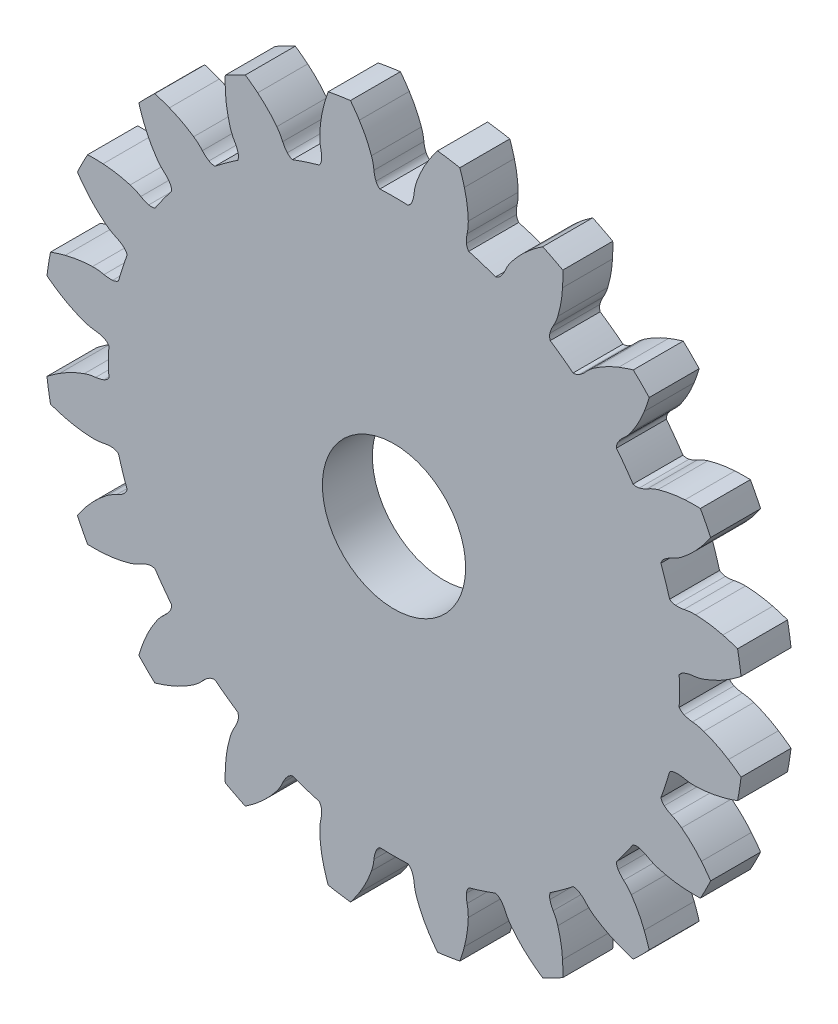
SolidWorks part; units mm, degrees
ref_plane "Front Plane" through (0, 0, 0) normal (0, 0, 1) x (1, 0, 0)
ref_plane "Top Plane" through (0, 0, 0) normal (0, 1, 0) x (1, 0, 0)
ref_plane "Right Plane" through (0, 0, 0) normal (1, 0, 0) x (0, 0, -1)
sketch "Model" plane through (0, 0, 0) normal (0, 0, 1) x (1, 0, 0)
  line L0 (-1.9599, -122.157) -> (1.9099, -120.8335)
  line L1 (1.9099, -120.8335) -> (1.9099, -119.1665)
  line L2 (1.9099, -119.1665) -> (-1.9599, -117.843)
  line L3 (-1.9599, -117.843) -> (-1.9599, -116.157)
  line L4 (-1.9599, -116.157) -> (1.9099, -114.8335)
  line L5 (1.9099, -114.8335) -> (1.9099, -113.1665)
  line L6 (1.9099, -113.1665) -> (-1.9599, -111.843)
  line L7 (-1.9599, -111.843) -> (-1.9599, -110.157)
  line L8 (-1.9599, -110.157) -> (1.9099, -108.8335)
  line L9 (1.9099, -108.8335) -> (1.9099, -107.1665)
  line L10 (1.9099, -107.1665) -> (-1.9599, -105.843)
  line L11 (-1.9599, -105.843) -> (-1.9599, -104.157)
  line L12 (-1.9599, -104.157) -> (1.9099, -102.8335)
  line L13 (1.9099, -102.8335) -> (1.9099, -101.1665)
  line L14 (1.9099, -101.1665) -> (-1.9599, -99.843)
  line L15 (-1.9599, -99.843) -> (-1.9599, -98.157)
  line L16 (-1.9599, -98.157) -> (1.9099, -96.8335)
  line L17 (1.9099, -96.8335) -> (1.9099, -95.1665)
  line L18 (1.9099, -95.1665) -> (-1.9599, -93.843)
  line L19 (-1.9599, -93.843) -> (-1.9599, -92.157)
  line L20 (-1.9599, -92.157) -> (1.9099, -90.8335)
  line L21 (1.9099, -90.8335) -> (1.9099, -89.1665)
  line L22 (1.9099, -89.1665) -> (-1.9599, -87.843)
  line L23 (-1.9599, -87.843) -> (-1.9599, -86.157)
  line L24 (-1.9599, -86.157) -> (1.9099, -84.8335)
  line L25 (1.9099, -84.8335) -> (1.9099, -83.1665)
  line L26 (1.9099, -83.1665) -> (-1.9599, -81.843)
  line L27 (-1.9599, -81.843) -> (-1.9599, -80.157)
  line L28 (-1.9599, -80.157) -> (1.9099, -78.8335)
  line L29 (1.9099, -78.8335) -> (1.9099, -77.1665)
  line L30 (1.9099, -77.1665) -> (-1.9599, -75.843)
  line L31 (-1.9599, -75.843) -> (-1.9599, -74.157)
  line L32 (-1.9599, -74.157) -> (1.9099, -72.8335)
  line L33 (1.9099, -72.8335) -> (1.9099, -71.1665)
  line L34 (1.9099, -71.1665) -> (-1.9599, -69.843)
  line L35 (-1.9599, -69.843) -> (-1.9599, -68.157)
  line L36 (-1.9599, -68.157) -> (1.9099, -66.8335)
  line L37 (1.9099, -66.8335) -> (1.9099, -65.1665)
  line L38 (1.9099, -65.1665) -> (-1.9599, -63.843)
  line L39 (-1.9599, -63.843) -> (-1.9599, -62.157)
  line L40 (-1.9599, -62.157) -> (1.9099, -60.8335)
  line L41 (1.9099, -60.8335) -> (1.9099, -59.1665)
  line L42 (1.9099, -59.1665) -> (-1.9599, -57.843)
  line L43 (-1.9599, -57.843) -> (-1.9599, -56.157)
  line L44 (-1.9599, -56.157) -> (1.9099, -54.8335)
  line L45 (1.9099, -54.8335) -> (1.9099, -53.1665)
  line L46 (1.9099, -53.1665) -> (-1.9599, -51.843)
  line L47 (-1.9599, -51.843) -> (-1.9599, -50.157)
  line L48 (-1.9599, -50.157) -> (1.9099, -48.8335)
  line L49 (1.9099, -48.8335) -> (1.9099, -47.1665)
  line L50 (1.9099, -47.1665) -> (-1.9599, -45.843)
  line L51 (-1.9599, -45.843) -> (-1.9599, -44.157)
  line L52 (-1.9599, -44.157) -> (1.9099, -42.8335)
  line L53 (1.9099, -42.8335) -> (1.9099, -41.1665)
  line L54 (1.9099, -41.1665) -> (-1.9599, -39.843)
  line L55 (-1.9599, -39.843) -> (-1.9599, -38.157)
  line L56 (-1.9599, -38.157) -> (1.9099, -36.8335)
  line L57 (1.9099, -36.8335) -> (1.9099, -35.1665)
  line L58 (1.9099, -35.1665) -> (-1.9599, -33.843)
  line L59 (-1.9599, -33.843) -> (-1.9599, -32.157)
  line L60 (-1.9599, -32.157) -> (1.9099, -30.8335)
  line L61 (1.9099, -30.8335) -> (1.9099, -29.1665)
  line L62 (1.9099, -29.1665) -> (-1.9599, -27.843)
  line L63 (-1.9599, -27.843) -> (-1.9599, -26.157)
  line L64 (-1.9599, -26.157) -> (1.9099, -24.8335)
  line L65 (1.9099, -24.8335) -> (1.9099, -23.1665)
  line L66 (1.9099, -23.1665) -> (-1.9599, -21.843)
  line L67 (-1.9599, -21.843) -> (-1.9599, -20.157)
  line L68 (-1.9599, -20.157) -> (1.9099, -18.8335)
  line L69 (1.9099, -18.8335) -> (1.9099, -17.1665)
  line L70 (1.9099, -17.1665) -> (-1.9599, -15.843)
  line L71 (-1.9599, -15.843) -> (-1.9599, -14.157)
  line L72 (-1.9599, -14.157) -> (1.9099, -12.8335)
  line L73 (1.9099, -12.8335) -> (1.9099, -11.1665)
  line L74 (1.9099, -11.1665) -> (-1.9599, -9.843)
  line L75 (-1.9599, -9.843) -> (-1.9599, -8.157)
  line L76 (-1.9599, -8.157) -> (1.9099, -6.8335)
  line L77 (1.9099, -6.8335) -> (1.9099, -5.1665)
  line L78 (1.9099, -5.1665) -> (-1.9599, -3.843)
  line L79 (-1.9599, -3.843) -> (-1.9599, -2.157)
  line L80 (-1.9599, -2.157) -> (1.9099, -0.8335)
  line L81 (1.9099, -0.8335) -> (1.9099, 0.8335)
  line L82 (1.9099, 0.8335) -> (-1.9599, 2.157)
  line L83 (-1.9599, 2.157) -> (-1.9599, 3.843)
  line L84 (-1.9599, 3.843) -> (1.9099, 5.1665)
  line L85 (1.9099, 5.1665) -> (1.9099, 6.8335)
  line L86 (1.9099, 6.8335) -> (-1.9599, 8.157)
  line L87 (-1.9599, 8.157) -> (-1.9599, 9.843)
  line L88 (-1.9599, 9.843) -> (1.9099, 11.1665)
  line L89 (1.9099, 11.1665) -> (1.9099, 12.8335)
  line L90 (1.9099, 12.8335) -> (-1.9599, 14.157)
  line L91 (-1.9599, 14.157) -> (-1.9599, 15.843)
  line L92 (-1.9599, 15.843) -> (1.9099, 17.1665)
  line L93 (1.9099, 17.1665) -> (1.9099, 18.8335)
  line L94 (1.9099, 18.8335) -> (-1.9599, 20.157)
  line L95 (-1.9599, 20.157) -> (-1.9599, 21.843)
  line L96 (-1.9599, 21.843) -> (1.9099, 23.1665)
  line L97 (1.9099, 23.1665) -> (1.9099, 24.8335)
  line L98 (1.9099, 24.8335) -> (-1.9599, 26.157)
  line L99 (-1.9599, 26.157) -> (-1.9599, 27.843)
  line L100 (-1.9599, 27.843) -> (1.9099, 29.1665)
  line L101 (1.9099, 29.1665) -> (1.9099, 30.8335)
  line L102 (1.9099, 30.8335) -> (-1.9599, 32.157)
  line L103 (-1.9599, 32.157) -> (-1.9599, 33.843)
  line L104 (-1.9599, 33.843) -> (1.9099, 35.1665)
  line L105 (1.9099, 35.1665) -> (1.9099, 36.8335)
  line L106 (1.9099, 36.8335) -> (-1.9599, 38.157)
  line L107 (-1.9599, 38.157) -> (-1.9599, 39.843)
  line L108 (-1.9599, 39.843) -> (1.9099, 41.1665)
  line L109 (1.9099, 41.1665) -> (1.9099, 42.8335)
  line L110 (1.9099, 42.8335) -> (-1.9599, 44.157)
  line L111 (-1.9599, 44.157) -> (-1.9599, 45.843)
  line L112 (-1.9599, 45.843) -> (1.9099, 47.1665)
  line L113 (1.9099, 47.1665) -> (1.9099, 48.8335)
  line L114 (1.9099, 48.8335) -> (-1.9599, 50.157)
  line L115 (-1.9599, 50.157) -> (-1.9599, 51.843)
  line L116 (-1.9599, 51.843) -> (1.9099, 53.1665)
  line L117 (1.9099, 53.1665) -> (1.9099, 54.8335)
  line L118 (1.9099, 54.8335) -> (-1.9599, 56.157)
  line L119 (-1.9599, 56.157) -> (-1.9599, 57.843)
  line L120 (-1.9599, 57.843) -> (1.9099, 59.1665)
  line L121 (1.9099, 59.1665) -> (1.9099, 60.8335)
  line L122 (1.9099, 60.8335) -> (-1.9599, 62.157)
  line L123 (-1.9599, 62.157) -> (-1.9599, 63.843)
  line L124 (-1.9599, 63.843) -> (1.9099, 65.1665)
  line L125 (1.9099, 65.1665) -> (1.9099, 66.8335)
  line L126 (1.9099, 66.8335) -> (-1.9599, 68.157)
  line L127 (-1.9599, 68.157) -> (-1.9599, 69.843)
  line L128 (-1.9599, 69.843) -> (1.9099, 71.1665)
  line L129 (1.9099, 71.1665) -> (1.9099, 72.8335)
  line L130 (1.9099, 72.8335) -> (-1.9599, 74.157)
  line L131 (-1.9599, 74.157) -> (-1.9599, 75.843)
  line L132 (-1.9599, 75.843) -> (1.9099, 77.1665)
  line L133 (1.9099, 77.1665) -> (1.9099, 78.8335)
  line L134 (1.9099, 78.8335) -> (-1.9599, 80.157)
  line L135 (-1.9599, 80.157) -> (-1.9599, 81.843)
  line L136 (-1.9599, 81.843) -> (1.9099, 83.1665)
  line L137 (1.9099, 83.1665) -> (1.9099, 84.8335)
  line L138 (1.9099, 84.8335) -> (-1.9599, 86.157)
  line L139 (-1.9599, 86.157) -> (-1.9599, 87.843)
  line L140 (-1.9599, 87.843) -> (1.9099, 89.1665)
  line L141 (1.9099, 89.1665) -> (1.9099, 90.8335)
  line L142 (1.9099, 90.8335) -> (-1.9599, 92.157)
  line L143 (-1.9599, 92.157) -> (-1.9599, 93.843)
  line L144 (-1.9599, 93.843) -> (1.9099, 95.1665)
  line L145 (1.9099, 95.1665) -> (1.9099, 96.8335)
  line L146 (1.9099, 96.8335) -> (-1.9599, 98.157)
  line L147 (-1.9599, 98.157) -> (-1.9599, 99.843)
  line L148 (-1.9599, 99.843) -> (1.9099, 101.1665)
  line L149 (1.9099, 101.1665) -> (1.9099, 102.8335)
  line L150 (1.9099, 102.8335) -> (-1.9599, 104.157)
  line L151 (-1.9599, 104.157) -> (-1.9599, 105.843)
  line L152 (-1.9599, 105.843) -> (1.9099, 107.1665)
  line L153 (1.9099, 107.1665) -> (1.9099, 108.8335)
  line L154 (1.9099, 108.8335) -> (-1.9599, 110.157)
  line L155 (-1.9599, 110.157) -> (-1.9599, 111.843)
  line L156 (-1.9599, 111.843) -> (1.9099, 113.1665)
  line L157 (1.9099, 113.1665) -> (1.9099, 114.8335)
  line L158 (1.9099, 114.8335) -> (-1.9599, 116.157)
  line L159 (-1.9599, 116.157) -> (-1.9599, 117.843)
  line L160 (-1.9599, 117.843) -> (1.9099, 119.1665)
  line L161 (1.9099, 119.1665) -> (1.9099, 120.8335)
  line L162 (1.9099, 120.8335) -> (-1.9599, 122.157)
  line L163 (-1.9599, 122.157) -> (-1.9599, 123)
  line L164 (-1.9599, 123) -> (-9.5993, 123)
  line L165 (-9.5993, 123) -> (-9.5993, -123)
  line L166 (-9.5993, -123) -> (-1.9599, -123)
  line L167 (-1.9599, -123) -> (-1.9599, -122.157)
  line L168 (-1.5377, 3.9366) -> (-1.6512, 3.2864)
  line L169 (-1.6512, 3.2864) -> (-1.7442, 2.6331)
  line L170 (-1.7442, 2.6331) -> (-1.7455, 2.6215)
  line L171 (-1.7455, 2.6215) -> (-1.7388, 2.6161)
  line L172 (-1.7388, 2.6161) -> (-1.4771, 2.4198)
  line L173 (-1.4771, 2.4198) -> (-1.2239, 2.242)
  line L174 (-1.2239, 2.242) -> (-0.9803, 2.082)
  line L175 (-0.9803, 2.082) -> (-0.7469, 1.9391)
  line L176 (-0.7469, 1.9391) -> (-0.5246, 1.8124)
  line L177 (-0.5246, 1.8124) -> (-0.3143, 1.7011)
  line L178 (-0.3143, 1.7011) -> (-0.1165, 1.6044)
  line L179 (-0.1165, 1.6044) -> (0.0679, 1.5212)
  line L180 (0.0679, 1.5212) -> (0.2383, 1.4506)
  line L181 (0.2383, 1.4506) -> (0.3942, 1.3918)
  line L182 (0.3942, 1.3918) -> (0.535, 1.3436)
  line L183 (0.535, 1.3436) -> (0.6602, 1.3051)
  line L184 (0.6602, 1.3051) -> (0.7694, 1.2753)
  line L185 (0.7694, 1.2753) -> (0.862, 1.2531)
  line L186 (0.862, 1.2531) -> (0.9379, 1.2374)
  line L187 (0.9379, 1.2374) -> (0.9966, 1.2272)
  line L188 (0.9966, 1.2272) -> (1.038, 1.2213)
  line L189 (1.038, 1.2213) -> (1.0618, 1.2187)
  line L190 (1.0618, 1.2187) -> (1.0916, 1.2164)
  line L191 (1.0916, 1.2164) -> (1.2696, 1.1958)
  line L192 (1.2696, 1.1958) -> (1.4284, 1.1659)
  line L193 (1.4284, 1.1659) -> (1.5676, 1.1277)
  line L194 (1.5676, 1.1277) -> (1.6869, 1.0826)
  line L195 (1.6869, 1.0826) -> (1.7859, 1.0316)
  line L196 (1.7859, 1.0316) -> (1.8646, 0.9761)
  line L197 (1.8646, 0.9761) -> (1.9226, 0.9172)
  line L198 (1.9226, 0.9172) -> (1.9599, 0.8563)
  line L199 (1.9599, 0.8563) -> (1.9764, 0.7945)
  line L200 (1.9764, 0.7945) -> (1.9599, 0.2692)
  line L201 (1.9599, 0.2692) -> (1.9599, -0.2692)
  line L202 (1.9599, -0.2692) -> (1.9764, -0.7945)
  line L203 (1.9764, -0.7945) -> (1.9599, -0.8563)
  line L204 (1.9599, -0.8563) -> (1.9226, -0.9172)
  line L205 (1.9226, -0.9172) -> (1.8646, -0.9761)
  line L206 (1.8646, -0.9761) -> (1.7859, -1.0316)
  line L207 (1.7859, -1.0316) -> (1.6869, -1.0826)
  line L208 (1.6869, -1.0826) -> (1.5676, -1.1277)
  line L209 (1.5676, -1.1277) -> (1.4284, -1.1659)
  line L210 (1.4284, -1.1659) -> (1.2696, -1.1958)
  line L211 (1.2696, -1.1958) -> (1.0916, -1.2164)
  line L212 (1.0916, -1.2164) -> (1.0618, -1.2187)
  line L213 (1.0618, -1.2187) -> (1.038, -1.2213)
  line L214 (1.038, -1.2213) -> (0.9966, -1.2272)
  line L215 (0.9966, -1.2272) -> (0.9379, -1.2374)
  line L216 (0.9379, -1.2374) -> (0.862, -1.2531)
  line L217 (0.862, -1.2531) -> (0.7694, -1.2753)
  line L218 (0.7694, -1.2753) -> (0.6602, -1.3051)
  line L219 (0.6602, -1.3051) -> (0.535, -1.3436)
  line L220 (0.535, -1.3436) -> (0.3942, -1.3918)
  line L221 (0.3942, -1.3918) -> (0.2383, -1.4506)
  line L222 (0.2383, -1.4506) -> (0.0679, -1.5212)
  line L223 (0.0679, -1.5212) -> (-0.1165, -1.6044)
  line L224 (-0.1165, -1.6044) -> (-0.3143, -1.7011)
  line L225 (-0.3143, -1.7011) -> (-0.5246, -1.8124)
  line L226 (-0.5246, -1.8124) -> (-0.7469, -1.9391)
  line L227 (-0.7469, -1.9391) -> (-0.9803, -2.082)
  line L228 (-0.9803, -2.082) -> (-1.2239, -2.242)
  line L229 (-1.2239, -2.242) -> (-1.4771, -2.4198)
  line L230 (-1.4771, -2.4198) -> (-1.7388, -2.6161)
  line L231 (-1.7388, -2.6161) -> (-1.7455, -2.6215)
  line L232 (-1.7455, -2.6215) -> (-1.7442, -2.6331)
  line L233 (-1.7442, -2.6331) -> (-1.6512, -3.2864)
  line L234 (-1.6512, -3.2864) -> (-1.5377, -3.9366)
  line L235 (-1.5377, -3.9366) -> (-1.5354, -3.948)
  line L236 (-1.5354, -3.948) -> (-1.5274, -3.951)
  line L237 (-1.5274, -3.951) -> (-1.2178, -4.0569)
  line L238 (-1.2178, -4.0569) -> (-0.9221, -4.1477)
  line L239 (-0.9221, -4.1477) -> (-0.6409, -4.2246)
  line L240 (-0.6409, -4.2246) -> (-0.3748, -4.2884)
  line L241 (-0.3748, -4.2884) -> (-0.1243, -4.3402)
  line L242 (-0.1243, -4.3402) -> (0.1102, -4.381)
  line L243 (0.1102, -4.381) -> (0.3281, -4.412)
  line L244 (0.3281, -4.412) -> (0.5292, -4.4341)
  line L245 (0.5292, -4.4341) -> (0.7132, -4.4485)
  line L246 (0.7132, -4.4485) -> (0.8796, -4.4563)
  line L247 (0.8796, -4.4563) -> (1.0284, -4.4586)
  line L248 (1.0284, -4.4586) -> (1.1593, -4.4565)
  line L249 (1.1593, -4.4565) -> (1.2724, -4.4511)
  line L250 (1.2724, -4.4511) -> (1.3673, -4.4436)
  line L251 (1.3673, -4.4436) -> (1.4443, -4.4351)
  line L252 (1.4443, -4.4351) -> (1.5034, -4.4267)
  line L253 (1.5034, -4.4267) -> (1.5445, -4.4195)
  line L254 (1.5445, -4.4195) -> (1.568, -4.4146)
  line L255 (1.568, -4.4146) -> (1.5971, -4.4076)
  line L256 (1.5971, -4.4076) -> (1.7727, -4.3722)
  line L257 (1.7727, -4.3722) -> (1.933, -4.3516)
  line L258 (1.933, -4.3516) -> (2.0771, -4.3448)
  line L259 (2.0771, -4.3448) -> (2.2045, -4.3509)
  line L260 (2.2045, -4.3509) -> (2.3145, -4.3688)
  line L261 (2.3145, -4.3688) -> (2.4064, -4.3973)
  line L262 (2.4064, -4.3973) -> (2.4798, -4.4353)
  line L263 (2.4798, -4.4353) -> (2.5341, -4.4818)
  line L264 (2.5341, -4.4818) -> (2.5689, -4.5354)
  line L265 (2.5689, -4.5354) -> (2.7155, -5.0401)
  line L266 (2.7155, -5.0401) -> (2.8819, -5.5522)
  line L267 (2.8819, -5.5522) -> (3.0599, -6.0467)
  line L268 (3.0599, -6.0467) -> (3.0633, -6.1105)
  line L269 (3.0633, -6.1105) -> (3.0467, -6.18)
  line L270 (3.0467, -6.18) -> (3.0097, -6.2539)
  line L271 (3.0097, -6.2539) -> (2.9521, -6.331)
  line L272 (2.9521, -6.331) -> (2.8736, -6.4101)
  line L273 (2.8736, -6.4101) -> (2.7741, -6.4899)
  line L274 (2.7741, -6.4899) -> (2.6535, -6.5692)
  line L275 (2.6535, -6.5692) -> (2.5118, -6.6468)
  line L276 (2.5118, -6.6468) -> (2.3488, -6.7213)
  line L277 (2.3488, -6.7213) -> (2.3212, -6.7327)
  line L278 (2.3212, -6.7327) -> (2.2993, -6.7426)
  line L279 (2.2993, -6.7426) -> (2.2618, -6.761)
  line L280 (2.2618, -6.761) -> (2.2091, -6.7888)
  line L281 (2.2091, -6.7888) -> (2.1418, -6.8272)
  line L282 (2.1418, -6.8272) -> (2.0605, -6.877)
  line L283 (2.0605, -6.877) -> (1.966, -6.939)
  line L284 (1.966, -6.939) -> (1.8588, -7.0143)
  line L285 (1.8588, -7.0143) -> (1.7398, -7.1036)
  line L286 (1.7398, -7.1036) -> (1.6097, -7.2078)
  line L287 (1.6097, -7.2078) -> (1.4694, -7.3275)
  line L288 (1.4694, -7.3275) -> (1.3197, -7.4636)
  line L289 (1.3197, -7.4636) -> (1.1616, -7.6168)
  line L290 (1.1616, -7.6168) -> (0.9959, -7.7876)
  line L291 (0.9959, -7.7876) -> (0.8236, -7.9768)
  line L292 (0.8236, -7.9768) -> (0.6459, -8.1848)
  line L293 (0.6459, -8.1848) -> (0.4635, -8.4123)
  line L294 (0.4635, -8.4123) -> (0.2777, -8.6596)
  line L295 (0.2777, -8.6596) -> (0.0895, -8.9272)
  line L296 (0.0895, -8.9272) -> (0.0848, -8.9344)
  line L297 (0.0848, -8.9344) -> (0.0896, -8.945)
  line L298 (0.0896, -8.945) -> (0.3799, -9.5376)
  line L299 (0.3799, -9.5376) -> (0.6887, -10.1209)
  line L300 (0.6887, -10.1209) -> (0.6945, -10.131)
  line L301 (0.6945, -10.131) -> (0.7031, -10.1314)
  line L302 (0.7031, -10.1314) -> (1.0302, -10.1364)
  line L303 (1.0302, -10.1364) -> (1.3395, -10.1315)
  line L304 (1.3395, -10.1315) -> (1.6307, -10.1177)
  line L305 (1.6307, -10.1177) -> (1.9035, -10.0961)
  line L306 (1.9035, -10.0961) -> (2.1578, -10.0679)
  line L307 (2.1578, -10.0679) -> (2.3934, -10.0343)
  line L308 (2.3934, -10.0343) -> (2.6102, -9.9964)
  line L309 (2.6102, -9.9964) -> (2.8083, -9.9553)
  line L310 (2.8083, -9.9553) -> (2.9877, -9.9122)
  line L311 (2.9877, -9.9122) -> (3.1484, -9.8682)
  line L312 (3.1484, -9.8682) -> (3.2906, -9.8244)
  line L313 (3.2906, -9.8244) -> (3.4145, -9.7819)
  line L314 (3.4145, -9.7819) -> (3.5203, -9.7419)
  line L315 (3.5203, -9.7419) -> (3.6083, -9.7054)
  line L316 (3.6083, -9.7054) -> (3.6789, -9.6735)
  line L317 (3.6789, -9.6735) -> (3.7324, -9.6473)
  line L318 (3.7324, -9.6473) -> (3.7694, -9.6277)
  line L319 (3.7694, -9.6277) -> (3.7902, -9.6158)
  line L320 (3.7902, -9.6158) -> (3.8157, -9.6002)
  line L321 (3.8157, -9.6002) -> (3.9718, -9.5122)
  line L322 (3.9718, -9.5122) -> (4.1178, -9.4431)
  line L323 (4.1178, -9.4431) -> (4.2529, -9.3921)
  line L324 (4.2529, -9.3921) -> (4.3759, -9.3585)
  line L325 (4.3759, -9.3585) -> (4.486, -9.3415)
  line L326 (4.486, -9.3415) -> (4.5822, -9.3402)
  line L327 (4.5822, -9.3402) -> (4.6638, -9.3538)
  line L328 (4.6638, -9.3538) -> (4.7297, -9.3811)
  line L329 (4.7297, -9.3811) -> (4.7794, -9.4214)
  line L330 (4.7794, -9.4214) -> (5.0748, -9.8561)
  line L331 (5.0748, -9.8561) -> (5.3913, -10.2917)
  line L332 (5.3913, -10.2917) -> (5.7134, -10.707)
  line L333 (5.7134, -10.707) -> (5.7364, -10.7667)
  line L334 (5.7364, -10.7667) -> (5.742, -10.8379)
  line L335 (5.742, -10.8379) -> (5.7297, -10.9196)
  line L336 (5.7297, -10.9196) -> (5.6987, -11.0107)
  line L337 (5.6987, -11.0107) -> (5.6485, -11.1102)
  line L338 (5.6485, -11.1102) -> (5.5786, -11.2168)
  line L339 (5.5786, -11.2168) -> (5.4884, -11.3295)
  line L340 (5.4884, -11.3295) -> (5.3775, -11.447)
  line L341 (5.3775, -11.447) -> (5.2456, -11.5683)
  line L342 (5.2456, -11.5683) -> (5.2228, -11.5877)
  line L343 (5.2228, -11.5877) -> (5.2051, -11.6038)
  line L344 (5.2051, -11.6038) -> (5.1751, -11.6329)
  line L345 (5.1751, -11.6329) -> (5.1336, -11.6757)
  line L346 (5.1336, -11.6757) -> (5.0815, -11.733)
  line L347 (5.0815, -11.733) -> (5.0195, -11.8054)
  line L348 (5.0195, -11.8054) -> (4.9488, -11.8937)
  line L349 (4.9488, -11.8937) -> (4.8701, -11.9984)
  line L350 (4.8701, -11.9984) -> (4.7845, -12.1201)
  line L351 (4.7845, -12.1201) -> (4.693, -12.2594)
  line L352 (4.693, -12.2594) -> (4.5965, -12.4166)
  line L353 (4.5965, -12.4166) -> (4.4962, -12.5923)
  line L354 (4.4962, -12.5923) -> (4.3932, -12.7868)
  line L355 (4.3932, -12.7868) -> (4.2884, -13.0005)
  line L356 (4.2884, -13.0005) -> (4.1831, -13.2337)
  line L357 (4.1831, -13.2337) -> (4.0782, -13.4865)
  line L358 (4.0782, -13.4865) -> (3.9751, -13.7591)
  line L359 (3.9751, -13.7591) -> (3.8748, -14.0517)
  line L360 (3.8748, -14.0517) -> (3.7785, -14.3644)
  line L361 (3.7785, -14.3644) -> (3.7763, -14.3727)
  line L362 (3.7763, -14.3727) -> (3.7841, -14.3813)
  line L363 (3.7841, -14.3813) -> (4.2434, -14.8552)
  line L364 (4.2434, -14.8552) -> (4.7173, -15.3145)
  line L365 (4.7173, -15.3145) -> (4.7259, -15.3223)
  line L366 (4.7259, -15.3223) -> (4.7342, -15.3201)
  line L367 (4.7342, -15.3201) -> (5.0469, -15.2238)
  line L368 (5.0469, -15.2238) -> (5.3395, -15.1235)
  line L369 (5.3395, -15.1235) -> (5.6121, -15.0203)
  line L370 (5.6121, -15.0203) -> (5.8649, -14.9155)
  line L371 (5.8649, -14.9155) -> (6.0981, -14.8102)
  line L372 (6.0981, -14.8102) -> (6.3117, -14.7054)
  line L373 (6.3117, -14.7054) -> (6.5063, -14.6023)
  line L374 (6.5063, -14.6023) -> (6.682, -14.5021)
  line L375 (6.682, -14.5021) -> (6.8392, -14.4056)
  line L376 (6.8392, -14.4056) -> (6.9785, -14.3141)
  line L377 (6.9785, -14.3141) -> (7.1002, -14.2285)
  line L378 (7.1002, -14.2285) -> (7.2049, -14.1498)
  line L379 (7.2049, -14.1498) -> (7.2932, -14.0791)
  line L380 (7.2932, -14.0791) -> (7.3656, -14.0171)
  line L381 (7.3656, -14.0171) -> (7.4229, -13.965)
  line L382 (7.4229, -13.965) -> (7.4657, -13.9235)
  line L383 (7.4657, -13.9235) -> (7.4948, -13.8935)
  line L384 (7.4948, -13.8935) -> (7.5109, -13.8758)
  line L385 (7.5109, -13.8758) -> (7.5303, -13.853)
  line L386 (7.5303, -13.853) -> (7.6515, -13.7211)
  line L387 (7.6515, -13.7211) -> (7.7691, -13.6102)
  line L388 (7.7691, -13.6102) -> (7.8818, -13.52)
  line L389 (7.8818, -13.52) -> (7.9884, -13.4501)
  line L390 (7.9884, -13.4501) -> (8.0879, -13.3999)
  line L391 (8.0879, -13.3999) -> (8.179, -13.3689)
  line L392 (8.179, -13.3689) -> (8.2607, -13.3566)
  line L393 (8.2607, -13.3566) -> (8.3319, -13.3622)
  line L394 (8.3319, -13.3622) -> (8.3916, -13.3852)
  line L395 (8.3916, -13.3852) -> (8.8069, -13.7073)
  line L396 (8.8069, -13.7073) -> (9.2425, -14.0238)
  line L397 (9.2425, -14.0238) -> (9.6772, -14.3192)
  line L398 (9.6772, -14.3192) -> (9.7175, -14.3688)
  line L399 (9.7175, -14.3688) -> (9.7448, -14.4348)
  line L400 (9.7448, -14.4348) -> (9.7584, -14.5164)
  line L401 (9.7584, -14.5164) -> (9.7571, -14.6126)
  line L402 (9.7571, -14.6126) -> (9.7401, -14.7227)
  line L403 (9.7401, -14.7227) -> (9.7065, -14.8457)
  line L404 (9.7065, -14.8457) -> (9.6555, -14.9808)
  line L405 (9.6555, -14.9808) -> (9.5864, -15.1268)
  line L406 (9.5864, -15.1268) -> (9.4984, -15.2829)
  line L407 (9.4984, -15.2829) -> (9.4828, -15.3084)
  line L408 (9.4828, -15.3084) -> (9.4709, -15.3292)
  line L409 (9.4709, -15.3292) -> (9.4513, -15.3661)
  line L410 (9.4513, -15.3661) -> (9.4251, -15.4197)
  line L411 (9.4251, -15.4197) -> (9.3932, -15.4903)
  line L412 (9.3932, -15.4903) -> (9.3567, -15.5783)
  line L413 (9.3567, -15.5783) -> (9.3167, -15.6841)
  line L414 (9.3167, -15.6841) -> (9.2742, -15.808)
  line L415 (9.2742, -15.808) -> (9.2304, -15.9502)
  line L416 (9.2304, -15.9502) -> (9.1864, -16.1109)
  line L417 (9.1864, -16.1109) -> (9.1433, -16.2903)
  line L418 (9.1433, -16.2903) -> (9.1022, -16.4884)
  line L419 (9.1022, -16.4884) -> (9.0643, -16.7052)
  line L420 (9.0643, -16.7052) -> (9.0307, -16.9408)
  line L421 (9.0307, -16.9408) -> (9.0025, -17.1951)
  line L422 (9.0025, -17.1951) -> (8.9809, -17.4679)
  line L423 (8.9809, -17.4679) -> (8.9671, -17.7591)
  line L424 (8.9671, -17.7591) -> (8.9622, -18.0684)
  line L425 (8.9622, -18.0684) -> (8.9672, -18.3955)
  line L426 (8.9672, -18.3955) -> (8.9676, -18.4041)
  line L427 (8.9676, -18.4041) -> (8.9777, -18.4098)
  line L428 (8.9777, -18.4098) -> (9.561, -18.7187)
  line L429 (9.561, -18.7187) -> (10.1536, -19.009)
  line L430 (10.1536, -19.009) -> (10.1642, -19.0138)
  line L431 (10.1642, -19.0138) -> (10.1714, -19.0091)
  line L432 (10.1714, -19.0091) -> (10.439, -18.8209)
  line L433 (10.439, -18.8209) -> (10.6863, -18.6351)
  line L434 (10.6863, -18.6351) -> (10.9138, -18.4527)
  line L435 (10.9138, -18.4527) -> (11.1218, -18.2749)
  line L436 (11.1218, -18.2749) -> (11.311, -18.1027)
  line L437 (11.311, -18.1027) -> (11.4818, -17.937)
  line L438 (11.4818, -17.937) -> (11.635, -17.7789)
  line L439 (11.635, -17.7789) -> (11.7711, -17.6292)
  line L440 (11.7711, -17.6292) -> (11.8908, -17.4889)
  line L441 (11.8908, -17.4889) -> (11.995, -17.3588)
  line L442 (11.995, -17.3588) -> (12.0843, -17.2398)
  line L443 (12.0843, -17.2398) -> (12.1596, -17.1326)
  line L444 (12.1596, -17.1326) -> (12.2216, -17.038)
  line L445 (12.2216, -17.038) -> (12.2714, -16.9568)
  line L446 (12.2714, -16.9568) -> (12.3098, -16.8895)
  line L447 (12.3098, -16.8895) -> (12.3376, -16.8368)
  line L448 (12.3376, -16.8368) -> (12.356, -16.7993)
  line L449 (12.356, -16.7993) -> (12.3659, -16.7774)
  line L450 (12.3659, -16.7774) -> (12.3773, -16.7498)
  line L451 (12.3773, -16.7498) -> (12.4518, -16.5868)
  line L452 (12.4518, -16.5868) -> (12.5294, -16.4451)
  line L453 (12.5294, -16.4451) -> (12.6087, -16.3245)
  line L454 (12.6087, -16.3245) -> (12.6885, -16.225)
  line L455 (12.6885, -16.225) -> (12.7676, -16.1465)
  line L456 (12.7676, -16.1465) -> (12.8447, -16.0889)
  line L457 (12.8447, -16.0889) -> (12.9186, -16.0519)
  line L458 (12.9186, -16.0519) -> (12.9881, -16.0353)
  line L459 (12.9881, -16.0353) -> (13.0519, -16.0387)
  line L460 (13.0519, -16.0387) -> (13.5464, -16.2167)
  line L461 (13.5464, -16.2167) -> (14.0585, -16.3831)
  line L462 (14.0585, -16.3831) -> (14.5632, -16.5297)
  line L463 (14.5632, -16.5297) -> (14.6168, -16.5645)
  line L464 (14.6168, -16.5645) -> (14.6633, -16.6188)
  line L465 (14.6633, -16.6188) -> (14.7013, -16.6922)
  line L466 (14.7013, -16.6922) -> (14.7298, -16.7841)
  line L467 (14.7298, -16.7841) -> (14.7477, -16.8941)
  line L468 (14.7477, -16.8941) -> (14.7538, -17.0214)
  line L469 (14.7538, -17.0214) -> (14.747, -17.1656)
  line L470 (14.747, -17.1656) -> (14.7264, -17.3259)
  line L471 (14.7264, -17.3259) -> (14.691, -17.5015)
  line L472 (14.691, -17.5015) -> (14.684, -17.5306)
  line L473 (14.684, -17.5306) -> (14.6791, -17.5541)
  line L474 (14.6791, -17.5541) -> (14.6719, -17.5952)
  line L475 (14.6719, -17.5952) -> (14.6635, -17.6543)
  line L476 (14.6635, -17.6543) -> (14.655, -17.7312)
  line L477 (14.655, -17.7312) -> (14.6475, -17.8262)
  line L478 (14.6475, -17.8262) -> (14.6421, -17.9392)
  line L479 (14.6421, -17.9392) -> (14.64, -18.0702)
  line L480 (14.64, -18.0702) -> (14.6423, -18.219)
  line L481 (14.6423, -18.219) -> (14.6501, -18.3854)
  line L482 (14.6501, -18.3854) -> (14.6645, -18.5693)
  line L483 (14.6645, -18.5693) -> (14.6866, -18.7704)
  line L484 (14.6866, -18.7704) -> (14.7176, -18.9884)
  line L485 (14.7176, -18.9884) -> (14.7584, -19.2229)
  line L486 (14.7584, -19.2229) -> (14.8102, -19.4734)
  line L487 (14.8102, -19.4734) -> (14.874, -19.7395)
  line L488 (14.874, -19.7395) -> (14.9508, -20.0207)
  line L489 (14.9508, -20.0207) -> (15.0417, -20.3164)
  line L490 (15.0417, -20.3164) -> (15.1476, -20.6259)
  line L491 (15.1476, -20.6259) -> (15.1506, -20.634)
  line L492 (15.1506, -20.634) -> (15.162, -20.6363)
  line L493 (15.162, -20.6363) -> (15.8121, -20.7498)
  line L494 (15.8121, -20.7498) -> (16.4655, -20.8428)
  line L495 (16.4655, -20.8428) -> (16.4771, -20.8441)
  line L496 (16.4771, -20.8441) -> (16.4825, -20.8374)
  line L497 (16.4825, -20.8374) -> (16.6788, -20.5757)
  line L498 (16.6788, -20.5757) -> (16.8566, -20.3225)
  line L499 (16.8566, -20.3225) -> (17.0166, -20.0789)
  line L500 (17.0166, -20.0789) -> (17.1595, -19.8455)
  line L501 (17.1595, -19.8455) -> (17.2862, -19.6232)
  line L502 (17.2862, -19.6232) -> (17.3974, -19.4129)
  line L503 (17.3974, -19.4129) -> (17.4942, -19.2151)
  line L504 (17.4942, -19.2151) -> (17.5774, -19.0307)
  line L505 (17.5774, -19.0307) -> (17.648, -18.8603)
  line L506 (17.648, -18.8603) -> (17.7068, -18.7044)
  line L507 (17.7068, -18.7044) -> (17.755, -18.5636)
  line L508 (17.755, -18.5636) -> (17.7935, -18.4384)
  line L509 (17.7935, -18.4384) -> (17.8233, -18.3292)
  line L510 (17.8233, -18.3292) -> (17.8455, -18.2366)
  line L511 (17.8455, -18.2366) -> (17.8612, -18.1607)
  line L512 (17.8612, -18.1607) -> (17.8714, -18.102)
  line L513 (17.8714, -18.102) -> (17.8773, -18.0606)
  line L514 (17.8773, -18.0606) -> (17.8799, -18.0368)
  line L515 (17.8799, -18.0368) -> (17.8822, -18.007)
  line L516 (17.8822, -18.007) -> (17.9028, -17.829)
  line L517 (17.9028, -17.829) -> (17.9327, -17.6702)
  line L518 (17.9327, -17.6702) -> (17.9709, -17.531)
  line L519 (17.9709, -17.531) -> (18.016, -17.4117)
  line L520 (18.016, -17.4117) -> (18.067, -17.3127)
  line L521 (18.067, -17.3127) -> (18.1225, -17.234)
  line L522 (18.1225, -17.234) -> (18.1814, -17.176)
  line L523 (18.1814, -17.176) -> (18.2423, -17.1387)
  line L524 (18.2423, -17.1387) -> (18.3041, -17.1222)
  line L525 (18.3041, -17.1222) -> (18.8294, -17.1387)
  line L526 (18.8294, -17.1387) -> (19.3678, -17.1387)
  line L527 (19.3678, -17.1387) -> (19.8931, -17.1222)
  line L528 (19.8931, -17.1222) -> (19.9549, -17.1387)
  line L529 (19.9549, -17.1387) -> (20.0158, -17.176)
  line L530 (20.0158, -17.176) -> (20.0747, -17.234)
  line L531 (20.0747, -17.234) -> (20.1302, -17.3127)
  line L532 (20.1302, -17.3127) -> (20.1812, -17.4117)
  line L533 (20.1812, -17.4117) -> (20.2263, -17.531)
  line L534 (20.2263, -17.531) -> (20.2645, -17.6702)
  line L535 (20.2645, -17.6702) -> (20.2944, -17.829)
  line L536 (20.2944, -17.829) -> (20.315, -18.007)
  line L537 (20.315, -18.007) -> (20.3173, -18.0368)
  line L538 (20.3173, -18.0368) -> (20.3199, -18.0606)
  line L539 (20.3199, -18.0606) -> (20.3258, -18.102)
  line L540 (20.3258, -18.102) -> (20.336, -18.1607)
  line L541 (20.336, -18.1607) -> (20.3517, -18.2366)
  line L542 (20.3517, -18.2366) -> (20.3739, -18.3292)
  line L543 (20.3739, -18.3292) -> (20.4037, -18.4384)
  line L544 (20.4037, -18.4384) -> (20.4422, -18.5636)
  line L545 (20.4422, -18.5636) -> (20.4904, -18.7044)
  line L546 (20.4904, -18.7044) -> (20.5492, -18.8603)
  line L547 (20.5492, -18.8603) -> (20.6198, -19.0307)
  line L548 (20.6198, -19.0307) -> (20.703, -19.2151)
  line L549 (20.703, -19.2151) -> (20.7997, -19.4129)
  line L550 (20.7997, -19.4129) -> (20.911, -19.6232)
  line L551 (20.911, -19.6232) -> (21.0377, -19.8455)
  line L552 (21.0377, -19.8455) -> (21.1806, -20.0789)
  line L553 (21.1806, -20.0789) -> (21.3406, -20.3225)
  line L554 (21.3406, -20.3225) -> (21.5184, -20.5757)
  line L555 (21.5184, -20.5757) -> (21.7147, -20.8374)
  line L556 (21.7147, -20.8374) -> (21.7201, -20.8441)
  line L557 (21.7201, -20.8441) -> (21.7317, -20.8428)
  line L558 (21.7317, -20.8428) -> (22.385, -20.7498)
  line L559 (22.385, -20.7498) -> (23.0352, -20.6363)
  line L560 (23.0352, -20.6363) -> (23.0466, -20.634)
  line L561 (23.0466, -20.634) -> (23.0496, -20.6259)
  line L562 (23.0496, -20.6259) -> (23.1555, -20.3164)
  line L563 (23.1555, -20.3164) -> (23.2463, -20.0207)
  line L564 (23.2463, -20.0207) -> (23.3232, -19.7395)
  line L565 (23.3232, -19.7395) -> (23.387, -19.4734)
  line L566 (23.387, -19.4734) -> (23.4388, -19.2229)
  line L567 (23.4388, -19.2229) -> (23.4796, -18.9884)
  line L568 (23.4796, -18.9884) -> (23.5106, -18.7704)
  line L569 (23.5106, -18.7704) -> (23.5327, -18.5693)
  line L570 (23.5327, -18.5693) -> (23.5471, -18.3854)
  line L571 (23.5471, -18.3854) -> (23.5549, -18.219)
  line L572 (23.5549, -18.219) -> (23.5572, -18.0702)
  line L573 (23.5572, -18.0702) -> (23.5551, -17.9392)
  line L574 (23.5551, -17.9392) -> (23.5497, -17.8262)
  line L575 (23.5497, -17.8262) -> (23.5422, -17.7312)
  line L576 (23.5422, -17.7312) -> (23.5337, -17.6543)
  line L577 (23.5337, -17.6543) -> (23.5253, -17.5952)
  line L578 (23.5253, -17.5952) -> (23.5181, -17.5541)
  line L579 (23.5181, -17.5541) -> (23.5132, -17.5306)
  line L580 (23.5132, -17.5306) -> (23.5062, -17.5015)
  line L581 (23.5062, -17.5015) -> (23.4708, -17.3259)
  line L582 (23.4708, -17.3259) -> (23.4502, -17.1656)
  line L583 (23.4502, -17.1656) -> (23.4434, -17.0214)
  line L584 (23.4434, -17.0214) -> (23.4495, -16.8941)
  line L585 (23.4495, -16.8941) -> (23.4674, -16.7841)
  line L586 (23.4674, -16.7841) -> (23.4959, -16.6922)
  line L587 (23.4959, -16.6922) -> (23.5339, -16.6188)
  line L588 (23.5339, -16.6188) -> (23.5804, -16.5645)
  line L589 (23.5804, -16.5645) -> (23.634, -16.5297)
  line L590 (23.634, -16.5297) -> (24.1387, -16.3831)
  line L591 (24.1387, -16.3831) -> (24.6508, -16.2167)
  line L592 (24.6508, -16.2167) -> (25.1453, -16.0387)
  line L593 (25.1453, -16.0387) -> (25.2091, -16.0353)
  line L594 (25.2091, -16.0353) -> (25.2786, -16.0519)
  line L595 (25.2786, -16.0519) -> (25.3525, -16.0889)
  line L596 (25.3525, -16.0889) -> (25.4296, -16.1465)
  line L597 (25.4296, -16.1465) -> (25.5087, -16.225)
  line L598 (25.5087, -16.225) -> (25.5885, -16.3245)
  line L599 (25.5885, -16.3245) -> (25.6678, -16.4451)
  line L600 (25.6678, -16.4451) -> (25.7453, -16.5868)
  line L601 (25.7453, -16.5868) -> (25.8199, -16.7498)
  line L602 (25.8199, -16.7498) -> (25.8313, -16.7774)
  line L603 (25.8313, -16.7774) -> (25.8412, -16.7993)
  line L604 (25.8412, -16.7993) -> (25.8595, -16.8368)
  line L605 (25.8595, -16.8368) -> (25.8874, -16.8895)
  line L606 (25.8874, -16.8895) -> (25.9258, -16.9568)
  line L607 (25.9258, -16.9568) -> (25.9755, -17.038)
  line L608 (25.9755, -17.038) -> (26.0376, -17.1326)
  line L609 (26.0376, -17.1326) -> (26.1129, -17.2398)
  line L610 (26.1129, -17.2398) -> (26.2022, -17.3588)
  line L611 (26.2022, -17.3588) -> (26.3064, -17.4889)
  line L612 (26.3064, -17.4889) -> (26.4261, -17.6292)
  line L613 (26.4261, -17.6292) -> (26.5622, -17.7789)
  line L614 (26.5622, -17.7789) -> (26.7154, -17.937)
  line L615 (26.7154, -17.937) -> (26.8862, -18.1027)
  line L616 (26.8862, -18.1027) -> (27.0754, -18.2749)
  line L617 (27.0754, -18.2749) -> (27.2834, -18.4527)
  line L618 (27.2834, -18.4527) -> (27.5109, -18.6351)
  line L619 (27.5109, -18.6351) -> (27.7582, -18.8209)
  line L620 (27.7582, -18.8209) -> (28.0258, -19.0091)
  line L621 (28.0258, -19.0091) -> (28.033, -19.0138)
  line L622 (28.033, -19.0138) -> (28.0436, -19.009)
  line L623 (28.0436, -19.009) -> (28.6362, -18.7187)
  line L624 (28.6362, -18.7187) -> (29.2195, -18.4098)
  line L625 (29.2195, -18.4098) -> (29.2296, -18.4041)
  line L626 (29.2296, -18.4041) -> (29.23, -18.3955)
  line L627 (29.23, -18.3955) -> (29.235, -18.0684)
  line L628 (29.235, -18.0684) -> (29.2301, -17.7591)
  line L629 (29.2301, -17.7591) -> (29.2162, -17.4679)
  line L630 (29.2162, -17.4679) -> (29.1947, -17.1951)
  line L631 (29.1947, -17.1951) -> (29.1665, -16.9408)
  line L632 (29.1665, -16.9408) -> (29.1329, -16.7052)
  line L633 (29.1329, -16.7052) -> (29.095, -16.4884)
  line L634 (29.095, -16.4884) -> (29.0539, -16.2903)
  line L635 (29.0539, -16.2903) -> (29.0108, -16.1109)
  line L636 (29.0108, -16.1109) -> (28.9668, -15.9502)
  line L637 (28.9668, -15.9502) -> (28.923, -15.808)
  line L638 (28.923, -15.808) -> (28.8805, -15.6841)
  line L639 (28.8805, -15.6841) -> (28.8405, -15.5783)
  line L640 (28.8405, -15.5783) -> (28.804, -15.4903)
  line L641 (28.804, -15.4903) -> (28.7721, -15.4197)
  line L642 (28.7721, -15.4197) -> (28.7459, -15.3661)
  line L643 (28.7459, -15.3661) -> (28.7263, -15.3292)
  line L644 (28.7263, -15.3292) -> (28.7144, -15.3084)
  line L645 (28.7144, -15.3084) -> (28.6988, -15.2829)
  line L646 (28.6988, -15.2829) -> (28.6108, -15.1268)
  line L647 (28.6108, -15.1268) -> (28.5416, -14.9808)
  line L648 (28.5416, -14.9808) -> (28.4907, -14.8457)
  line L649 (28.4907, -14.8457) -> (28.4571, -14.7227)
  line L650 (28.4571, -14.7227) -> (28.4401, -14.6126)
  line L651 (28.4401, -14.6126) -> (28.4388, -14.5164)
  line L652 (28.4388, -14.5164) -> (28.4523, -14.4348)
  line L653 (28.4523, -14.4348) -> (28.4797, -14.3688)
  line L654 (28.4797, -14.3688) -> (28.52, -14.3192)
  line L655 (28.52, -14.3192) -> (28.9547, -14.0238)
  line L656 (28.9547, -14.0238) -> (29.3903, -13.7073)
  line L657 (29.3903, -13.7073) -> (29.8056, -13.3852)
  line L658 (29.8056, -13.3852) -> (29.8652, -13.3622)
  line L659 (29.8652, -13.3622) -> (29.9365, -13.3566)
  line L660 (29.9365, -13.3566) -> (30.0182, -13.3689)
  line L661 (30.0182, -13.3689) -> (30.1093, -13.3999)
  line L662 (30.1093, -13.3999) -> (30.2088, -13.4501)
  line L663 (30.2088, -13.4501) -> (30.3154, -13.52)
  line L664 (30.3154, -13.52) -> (30.4281, -13.6102)
  line L665 (30.4281, -13.6102) -> (30.5456, -13.7211)
  line L666 (30.5456, -13.7211) -> (30.6669, -13.853)
  line L667 (30.6669, -13.853) -> (30.6863, -13.8758)
  line L668 (30.6863, -13.8758) -> (30.7024, -13.8935)
  line L669 (30.7024, -13.8935) -> (30.7315, -13.9235)
  line L670 (30.7315, -13.9235) -> (30.7743, -13.965)
  line L671 (30.7743, -13.965) -> (30.8316, -14.0171)
  line L672 (30.8316, -14.0171) -> (30.904, -14.0791)
  line L673 (30.904, -14.0791) -> (30.9923, -14.1498)
  line L674 (30.9923, -14.1498) -> (31.097, -14.2285)
  line L675 (31.097, -14.2285) -> (31.2187, -14.3141)
  line L676 (31.2187, -14.3141) -> (31.3579, -14.4056)
  line L677 (31.3579, -14.4056) -> (31.5152, -14.5021)
  line L678 (31.5152, -14.5021) -> (31.6909, -14.6023)
  line L679 (31.6909, -14.6023) -> (31.8854, -14.7054)
  line L680 (31.8854, -14.7054) -> (32.0991, -14.8102)
  line L681 (32.0991, -14.8102) -> (32.3323, -14.9155)
  line L682 (32.3323, -14.9155) -> (32.585, -15.0203)
  line L683 (32.585, -15.0203) -> (32.8577, -15.1235)
  line L684 (32.8577, -15.1235) -> (33.1503, -15.2238)
  line L685 (33.1503, -15.2238) -> (33.463, -15.3201)
  line L686 (33.463, -15.3201) -> (33.4713, -15.3223)
  line L687 (33.4713, -15.3223) -> (33.4799, -15.3145)
  line L688 (33.4799, -15.3145) -> (33.9538, -14.8552)
  line L689 (33.9538, -14.8552) -> (34.4131, -14.3813)
  line L690 (34.4131, -14.3813) -> (34.4209, -14.3727)
  line L691 (34.4209, -14.3727) -> (34.4187, -14.3644)
  line L692 (34.4187, -14.3644) -> (34.3224, -14.0517)
  line L693 (34.3224, -14.0517) -> (34.2221, -13.7591)
  line L694 (34.2221, -13.7591) -> (34.1189, -13.4865)
  line L695 (34.1189, -13.4865) -> (34.0141, -13.2337)
  line L696 (34.0141, -13.2337) -> (33.9088, -13.0005)
  line L697 (33.9088, -13.0005) -> (33.804, -12.7868)
  line L698 (33.804, -12.7868) -> (33.7009, -12.5923)
  line L699 (33.7009, -12.5923) -> (33.6006, -12.4166)
  line L700 (33.6006, -12.4166) -> (33.5042, -12.2594)
  line L701 (33.5042, -12.2594) -> (33.4127, -12.1201)
  line L702 (33.4127, -12.1201) -> (33.3271, -11.9984)
  line L703 (33.3271, -11.9984) -> (33.2484, -11.8937)
  line L704 (33.2484, -11.8937) -> (33.1776, -11.8054)
  line L705 (33.1776, -11.8054) -> (33.1157, -11.733)
  line L706 (33.1157, -11.733) -> (33.0636, -11.6757)
  line L707 (33.0636, -11.6757) -> (33.0221, -11.6329)
  line L708 (33.0221, -11.6329) -> (32.9921, -11.6038)
  line L709 (32.9921, -11.6038) -> (32.9744, -11.5877)
  line L710 (32.9744, -11.5877) -> (32.9516, -11.5683)
  line L711 (32.9516, -11.5683) -> (32.8196, -11.447)
  line L712 (32.8196, -11.447) -> (32.7088, -11.3295)
  line L713 (32.7088, -11.3295) -> (32.6186, -11.2168)
  line L714 (32.6186, -11.2168) -> (32.5486, -11.1102)
  line L715 (32.5486, -11.1102) -> (32.4985, -11.0107)
  line L716 (32.4985, -11.0107) -> (32.4675, -10.9196)
  line L717 (32.4675, -10.9196) -> (32.4551, -10.8379)
  line L718 (32.4551, -10.8379) -> (32.4608, -10.7667)
  line L719 (32.4608, -10.7667) -> (32.4838, -10.707)
  line L720 (32.4838, -10.707) -> (32.8059, -10.2917)
  line L721 (32.8059, -10.2917) -> (33.1224, -9.8561)
  line L722 (33.1224, -9.8561) -> (33.4178, -9.4214)
  line L723 (33.4178, -9.4214) -> (33.4674, -9.3811)
  line L724 (33.4674, -9.3811) -> (33.5334, -9.3538)
  line L725 (33.5334, -9.3538) -> (33.6149, -9.3402)
  line L726 (33.6149, -9.3402) -> (33.7112, -9.3415)
  line L727 (33.7112, -9.3415) -> (33.8213, -9.3585)
  line L728 (33.8213, -9.3585) -> (33.9443, -9.3921)
  line L729 (33.9443, -9.3921) -> (34.0794, -9.4431)
  line L730 (34.0794, -9.4431) -> (34.2254, -9.5122)
  line L731 (34.2254, -9.5122) -> (34.3815, -9.6002)
  line L732 (34.3815, -9.6002) -> (34.407, -9.6158)
  line L733 (34.407, -9.6158) -> (34.4278, -9.6277)
  line L734 (34.4278, -9.6277) -> (34.4647, -9.6473)
  line L735 (34.4647, -9.6473) -> (34.5183, -9.6735)
  line L736 (34.5183, -9.6735) -> (34.5889, -9.7054)
  line L737 (34.5889, -9.7054) -> (34.6769, -9.7419)
  line L738 (34.6769, -9.7419) -> (34.7827, -9.7819)
  line L739 (34.7827, -9.7819) -> (34.9066, -9.8244)
  line L740 (34.9066, -9.8244) -> (35.0488, -9.8682)
  line L741 (35.0488, -9.8682) -> (35.2095, -9.9122)
  line L742 (35.2095, -9.9122) -> (35.3889, -9.9553)
  line L743 (35.3889, -9.9553) -> (35.587, -9.9964)
  line L744 (35.587, -9.9964) -> (35.8038, -10.0343)
  line L745 (35.8038, -10.0343) -> (36.0394, -10.0679)
  line L746 (36.0394, -10.0679) -> (36.2937, -10.0961)
  line L747 (36.2937, -10.0961) -> (36.5665, -10.1177)
  line L748 (36.5665, -10.1177) -> (36.8577, -10.1315)
  line L749 (36.8577, -10.1315) -> (37.167, -10.1364)
  line L750 (37.167, -10.1364) -> (37.4941, -10.1314)
  line L751 (37.4941, -10.1314) -> (37.5027, -10.131)
  line L752 (37.5027, -10.131) -> (37.5084, -10.1209)
  line L753 (37.5084, -10.1209) -> (37.8173, -9.5376)
  line L754 (37.8173, -9.5376) -> (38.1076, -8.945)
  line L755 (38.1076, -8.945) -> (38.1124, -8.9344)
  line L756 (38.1124, -8.9344) -> (38.1077, -8.9272)
  line L757 (38.1077, -8.9272) -> (37.9195, -8.6596)
  line L758 (37.9195, -8.6596) -> (37.7337, -8.4123)
  line L759 (37.7337, -8.4123) -> (37.5513, -8.1848)
  line L760 (37.5513, -8.1848) -> (37.3735, -7.9768)
  line L761 (37.3735, -7.9768) -> (37.2013, -7.7876)
  line L762 (37.2013, -7.7876) -> (37.0356, -7.6168)
  line L763 (37.0356, -7.6168) -> (36.8775, -7.4636)
  line L764 (36.8775, -7.4636) -> (36.7278, -7.3275)
  line L765 (36.7278, -7.3275) -> (36.5875, -7.2078)
  line L766 (36.5875, -7.2078) -> (36.4574, -7.1036)
  line L767 (36.4574, -7.1036) -> (36.3384, -7.0143)
  line L768 (36.3384, -7.0143) -> (36.2312, -6.939)
  line L769 (36.2312, -6.939) -> (36.1366, -6.877)
  line L770 (36.1366, -6.877) -> (36.0554, -6.8272)
  line L771 (36.0554, -6.8272) -> (35.9881, -6.7888)
  line L772 (35.9881, -6.7888) -> (35.9354, -6.761)
  line L773 (35.9354, -6.761) -> (35.8979, -6.7426)
  line L774 (35.8979, -6.7426) -> (35.876, -6.7327)
  line L775 (35.876, -6.7327) -> (35.8483, -6.7213)
  line L776 (35.8483, -6.7213) -> (35.6854, -6.6468)
  line L777 (35.6854, -6.6468) -> (35.5437, -6.5692)
  line L778 (35.5437, -6.5692) -> (35.4231, -6.4899)
  line L779 (35.4231, -6.4899) -> (35.3236, -6.4101)
  line L780 (35.3236, -6.4101) -> (35.2451, -6.331)
  line L781 (35.2451, -6.331) -> (35.1875, -6.2539)
  line L782 (35.1875, -6.2539) -> (35.1505, -6.18)
  line L783 (35.1505, -6.18) -> (35.1339, -6.1105)
  line L784 (35.1339, -6.1105) -> (35.1373, -6.0467)
  line L785 (35.1373, -6.0467) -> (35.3153, -5.5522)
  line L786 (35.3153, -5.5522) -> (35.4817, -5.0401)
  line L787 (35.4817, -5.0401) -> (35.6283, -4.5354)
  line L788 (35.6283, -4.5354) -> (35.6631, -4.4818)
  line L789 (35.6631, -4.4818) -> (35.7174, -4.4353)
  line L790 (35.7174, -4.4353) -> (35.7908, -4.3973)
  line L791 (35.7908, -4.3973) -> (35.8827, -4.3688)
  line L792 (35.8827, -4.3688) -> (35.9926, -4.3509)
  line L793 (35.9926, -4.3509) -> (36.12, -4.3448)
  line L794 (36.12, -4.3448) -> (36.2642, -4.3516)
  line L795 (36.2642, -4.3516) -> (36.4245, -4.3722)
  line L796 (36.4245, -4.3722) -> (36.6001, -4.4076)
  line L797 (36.6001, -4.4076) -> (36.6292, -4.4146)
  line L798 (36.6292, -4.4146) -> (36.6527, -4.4195)
  line L799 (36.6527, -4.4195) -> (36.6938, -4.4267)
  line L800 (36.6938, -4.4267) -> (36.7529, -4.4351)
  line L801 (36.7529, -4.4351) -> (36.8298, -4.4436)
  line L802 (36.8298, -4.4436) -> (36.9248, -4.4511)
  line L803 (36.9248, -4.4511) -> (37.0378, -4.4565)
  line L804 (37.0378, -4.4565) -> (37.1688, -4.4586)
  line L805 (37.1688, -4.4586) -> (37.3176, -4.4563)
  line L806 (37.3176, -4.4563) -> (37.484, -4.4485)
  line L807 (37.484, -4.4485) -> (37.6679, -4.4341)
  line L808 (37.6679, -4.4341) -> (37.869, -4.412)
  line L809 (37.869, -4.412) -> (38.087, -4.381)
  line L810 (38.087, -4.381) -> (38.3215, -4.3402)
  line L811 (38.3215, -4.3402) -> (38.572, -4.2884)
  line L812 (38.572, -4.2884) -> (38.8381, -4.2246)
  line L813 (38.8381, -4.2246) -> (39.1193, -4.1477)
  line L814 (39.1193, -4.1477) -> (39.415, -4.0569)
  line L815 (39.415, -4.0569) -> (39.7245, -3.951)
  line L816 (39.7245, -3.951) -> (39.7326, -3.948)
  line L817 (39.7326, -3.948) -> (39.7349, -3.9366)
  line L818 (39.7349, -3.9366) -> (39.8484, -3.2864)
  line L819 (39.8484, -3.2864) -> (39.9414, -2.6331)
  line L820 (39.9414, -2.6331) -> (39.9427, -2.6215)
  line L821 (39.9427, -2.6215) -> (39.936, -2.6161)
  line L822 (39.936, -2.6161) -> (39.6743, -2.4198)
  line L823 (39.6743, -2.4198) -> (39.4211, -2.242)
  line L824 (39.4211, -2.242) -> (39.1774, -2.082)
  line L825 (39.1774, -2.082) -> (38.9441, -1.9391)
  line L826 (38.9441, -1.9391) -> (38.7218, -1.8124)
  line L827 (38.7218, -1.8124) -> (38.5115, -1.7011)
  line L828 (38.5115, -1.7011) -> (38.3137, -1.6044)
  line L829 (38.3137, -1.6044) -> (38.1293, -1.5212)
  line L830 (38.1293, -1.5212) -> (37.9588, -1.4506)
  line L831 (37.9588, -1.4506) -> (37.8029, -1.3918)
  line L832 (37.8029, -1.3918) -> (37.6622, -1.3436)
  line L833 (37.6622, -1.3436) -> (37.537, -1.3051)
  line L834 (37.537, -1.3051) -> (37.4278, -1.2753)
  line L835 (37.4278, -1.2753) -> (37.3352, -1.2531)
  line L836 (37.3352, -1.2531) -> (37.2593, -1.2374)
  line L837 (37.2593, -1.2374) -> (37.2006, -1.2272)
  line L838 (37.2006, -1.2272) -> (37.1592, -1.2213)
  line L839 (37.1592, -1.2213) -> (37.1354, -1.2187)
  line L840 (37.1354, -1.2187) -> (37.1055, -1.2164)
  line L841 (37.1055, -1.2164) -> (36.9276, -1.1958)
  line L842 (36.9276, -1.1958) -> (36.7688, -1.1659)
  line L843 (36.7688, -1.1659) -> (36.6296, -1.1277)
  line L844 (36.6296, -1.1277) -> (36.5103, -1.0826)
  line L845 (36.5103, -1.0826) -> (36.4112, -1.0316)
  line L846 (36.4112, -1.0316) -> (36.3326, -0.9761)
  line L847 (36.3326, -0.9761) -> (36.2746, -0.9172)
  line L848 (36.2746, -0.9172) -> (36.2373, -0.8563)
  line L849 (36.2373, -0.8563) -> (36.2208, -0.7945)
  line L850 (36.2208, -0.7945) -> (36.2373, -0.2692)
  line L851 (36.2373, -0.2692) -> (36.2373, 0.2692)
  line L852 (36.2373, 0.2692) -> (36.2208, 0.7945)
  line L853 (36.2208, 0.7945) -> (36.2373, 0.8563)
  line L854 (36.2373, 0.8563) -> (36.2746, 0.9172)
  line L855 (36.2746, 0.9172) -> (36.3326, 0.9761)
  line L856 (36.3326, 0.9761) -> (36.4112, 1.0316)
  line L857 (36.4112, 1.0316) -> (36.5103, 1.0826)
  line L858 (36.5103, 1.0826) -> (36.6296, 1.1277)
  line L859 (36.6296, 1.1277) -> (36.7688, 1.1659)
  line L860 (36.7688, 1.1659) -> (36.9276, 1.1958)
  line L861 (36.9276, 1.1958) -> (37.1055, 1.2164)
  line L862 (37.1055, 1.2164) -> (37.1354, 1.2187)
  line L863 (37.1354, 1.2187) -> (37.1592, 1.2213)
  line L864 (37.1592, 1.2213) -> (37.2006, 1.2272)
  line L865 (37.2006, 1.2272) -> (37.2593, 1.2374)
  line L866 (37.2593, 1.2374) -> (37.3352, 1.2531)
  line L867 (37.3352, 1.2531) -> (37.4278, 1.2753)
  line L868 (37.4278, 1.2753) -> (37.537, 1.3051)
  line L869 (37.537, 1.3051) -> (37.6622, 1.3436)
  line L870 (37.6622, 1.3436) -> (37.8029, 1.3918)
  line L871 (37.8029, 1.3918) -> (37.9588, 1.4506)
  line L872 (37.9588, 1.4506) -> (38.1293, 1.5212)
  line L873 (38.1293, 1.5212) -> (38.3137, 1.6044)
  line L874 (38.3137, 1.6044) -> (38.5115, 1.7011)
  line L875 (38.5115, 1.7011) -> (38.7218, 1.8124)
  line L876 (38.7218, 1.8124) -> (38.9441, 1.9391)
  line L877 (38.9441, 1.9391) -> (39.1774, 2.082)
  line L878 (39.1774, 2.082) -> (39.4211, 2.242)
  line L879 (39.4211, 2.242) -> (39.6743, 2.4198)
  line L880 (39.6743, 2.4198) -> (39.936, 2.6161)
  line L881 (39.936, 2.6161) -> (39.9427, 2.6215)
  line L882 (39.9427, 2.6215) -> (39.9414, 2.6331)
  line L883 (39.9414, 2.6331) -> (39.8484, 3.2864)
  line L884 (39.8484, 3.2864) -> (39.7349, 3.9366)
  line L885 (39.7349, 3.9366) -> (39.7326, 3.948)
  line L886 (39.7326, 3.948) -> (39.7245, 3.951)
  line L887 (39.7245, 3.951) -> (39.415, 4.0569)
  line L888 (39.415, 4.0569) -> (39.1193, 4.1477)
  line L889 (39.1193, 4.1477) -> (38.8381, 4.2246)
  line L890 (38.8381, 4.2246) -> (38.572, 4.2884)
  line L891 (38.572, 4.2884) -> (38.3215, 4.3402)
  line L892 (38.3215, 4.3402) -> (38.087, 4.381)
  line L893 (38.087, 4.381) -> (37.869, 4.412)
  line L894 (37.869, 4.412) -> (37.6679, 4.4341)
  line L895 (37.6679, 4.4341) -> (37.484, 4.4485)
  line L896 (37.484, 4.4485) -> (37.3176, 4.4563)
  line L897 (37.3176, 4.4563) -> (37.1688, 4.4586)
  line L898 (37.1688, 4.4586) -> (37.0378, 4.4565)
  line L899 (37.0378, 4.4565) -> (36.9248, 4.4511)
  line L900 (36.9248, 4.4511) -> (36.8298, 4.4436)
  line L901 (36.8298, 4.4436) -> (36.7529, 4.4351)
  line L902 (36.7529, 4.4351) -> (36.6938, 4.4267)
  line L903 (36.6938, 4.4267) -> (36.6527, 4.4195)
  line L904 (36.6527, 4.4195) -> (36.6292, 4.4146)
  line L905 (36.6292, 4.4146) -> (36.6001, 4.4076)
  line L906 (36.6001, 4.4076) -> (36.4245, 4.3722)
  line L907 (36.4245, 4.3722) -> (36.2642, 4.3516)
  line L908 (36.2642, 4.3516) -> (36.12, 4.3448)
  line L909 (36.12, 4.3448) -> (35.9926, 4.3509)
  line L910 (35.9926, 4.3509) -> (35.8827, 4.3688)
  line L911 (35.8827, 4.3688) -> (35.7908, 4.3973)
  line L912 (35.7908, 4.3973) -> (35.7174, 4.4353)
  line L913 (35.7174, 4.4353) -> (35.6631, 4.4818)
  line L914 (35.6631, 4.4818) -> (35.6283, 4.5354)
  line L915 (35.6283, 4.5354) -> (35.4817, 5.0401)
  line L916 (35.4817, 5.0401) -> (35.3153, 5.5522)
  line L917 (35.3153, 5.5522) -> (35.1373, 6.0467)
  line L918 (35.1373, 6.0467) -> (35.1339, 6.1105)
  line L919 (35.1339, 6.1105) -> (35.1505, 6.18)
  line L920 (35.1505, 6.18) -> (35.1875, 6.2539)
  line L921 (35.1875, 6.2539) -> (35.2451, 6.331)
  line L922 (35.2451, 6.331) -> (35.3236, 6.4101)
  line L923 (35.3236, 6.4101) -> (35.4231, 6.4899)
  line L924 (35.4231, 6.4899) -> (35.5437, 6.5692)
  line L925 (35.5437, 6.5692) -> (35.6854, 6.6468)
  line L926 (35.6854, 6.6468) -> (35.8483, 6.7213)
  line L927 (35.8483, 6.7213) -> (35.876, 6.7327)
  line L928 (35.876, 6.7327) -> (35.8979, 6.7426)
  line L929 (35.8979, 6.7426) -> (35.9354, 6.761)
  line L930 (35.9354, 6.761) -> (35.9881, 6.7888)
  line L931 (35.9881, 6.7888) -> (36.0554, 6.8272)
  line L932 (36.0554, 6.8272) -> (36.1366, 6.877)
  line L933 (36.1366, 6.877) -> (36.2312, 6.939)
  line L934 (36.2312, 6.939) -> (36.3384, 7.0143)
  line L935 (36.3384, 7.0143) -> (36.4574, 7.1036)
  line L936 (36.4574, 7.1036) -> (36.5875, 7.2078)
  line L937 (36.5875, 7.2078) -> (36.7278, 7.3275)
  line L938 (36.7278, 7.3275) -> (36.8775, 7.4636)
  line L939 (36.8775, 7.4636) -> (37.0356, 7.6168)
  line L940 (37.0356, 7.6168) -> (37.2013, 7.7876)
  line L941 (37.2013, 7.7876) -> (37.3735, 7.9768)
  line L942 (37.3735, 7.9768) -> (37.5513, 8.1848)
  line L943 (37.5513, 8.1848) -> (37.7337, 8.4123)
  line L944 (37.7337, 8.4123) -> (37.9195, 8.6596)
  line L945 (37.9195, 8.6596) -> (38.1077, 8.9272)
  line L946 (38.1077, 8.9272) -> (38.1124, 8.9344)
  line L947 (38.1124, 8.9344) -> (38.1076, 8.945)
  line L948 (38.1076, 8.945) -> (37.8173, 9.5376)
  line L949 (37.8173, 9.5376) -> (37.5084, 10.1209)
  line L950 (37.5084, 10.1209) -> (37.5027, 10.131)
  line L951 (37.5027, 10.131) -> (37.4941, 10.1314)
  line L952 (37.4941, 10.1314) -> (37.167, 10.1364)
  line L953 (37.167, 10.1364) -> (36.8577, 10.1315)
  line L954 (36.8577, 10.1315) -> (36.5665, 10.1177)
  line L955 (36.5665, 10.1177) -> (36.2937, 10.0961)
  line L956 (36.2937, 10.0961) -> (36.0394, 10.0679)
  line L957 (36.0394, 10.0679) -> (35.8038, 10.0343)
  line L958 (35.8038, 10.0343) -> (35.587, 9.9964)
  line L959 (35.587, 9.9964) -> (35.3889, 9.9553)
  line L960 (35.3889, 9.9553) -> (35.2095, 9.9122)
  line L961 (35.2095, 9.9122) -> (35.0488, 9.8682)
  line L962 (35.0488, 9.8682) -> (34.9066, 9.8244)
  line L963 (34.9066, 9.8244) -> (34.7827, 9.7819)
  line L964 (34.7827, 9.7819) -> (34.6769, 9.7419)
  line L965 (34.6769, 9.7419) -> (34.5889, 9.7054)
  line L966 (34.5889, 9.7054) -> (34.5183, 9.6735)
  line L967 (34.5183, 9.6735) -> (34.4647, 9.6473)
  line L968 (34.4647, 9.6473) -> (34.4278, 9.6277)
  line L969 (34.4278, 9.6277) -> (34.407, 9.6158)
  line L970 (34.407, 9.6158) -> (34.3815, 9.6002)
  line L971 (34.3815, 9.6002) -> (34.2254, 9.5122)
  line L972 (34.2254, 9.5122) -> (34.0794, 9.4431)
  line L973 (34.0794, 9.4431) -> (33.9443, 9.3921)
  line L974 (33.9443, 9.3921) -> (33.8213, 9.3585)
  line L975 (33.8213, 9.3585) -> (33.7112, 9.3415)
  line L976 (33.7112, 9.3415) -> (33.6149, 9.3402)
  line L977 (33.6149, 9.3402) -> (33.5334, 9.3538)
  line L978 (33.5334, 9.3538) -> (33.4674, 9.3811)
  line L979 (33.4674, 9.3811) -> (33.4178, 9.4214)
  line L980 (33.4178, 9.4214) -> (33.1224, 9.8561)
  line L981 (33.1224, 9.8561) -> (32.8059, 10.2917)
  line L982 (32.8059, 10.2917) -> (32.4838, 10.707)
  line L983 (32.4838, 10.707) -> (32.4608, 10.7667)
  line L984 (32.4608, 10.7667) -> (32.4551, 10.8379)
  line L985 (32.4551, 10.8379) -> (32.4675, 10.9196)
  line L986 (32.4675, 10.9196) -> (32.4985, 11.0107)
  line L987 (32.4985, 11.0107) -> (32.5486, 11.1102)
  line L988 (32.5486, 11.1102) -> (32.6186, 11.2168)
  line L989 (32.6186, 11.2168) -> (32.7088, 11.3295)
  line L990 (32.7088, 11.3295) -> (32.8196, 11.447)
  line L991 (32.8196, 11.447) -> (32.9516, 11.5683)
  line L992 (32.9516, 11.5683) -> (32.9744, 11.5877)
  line L993 (32.9744, 11.5877) -> (32.9921, 11.6038)
  line L994 (32.9921, 11.6038) -> (33.0221, 11.6329)
  line L995 (33.0221, 11.6329) -> (33.0636, 11.6757)
  line L996 (33.0636, 11.6757) -> (33.1157, 11.733)
  line L997 (33.1157, 11.733) -> (33.1776, 11.8054)
  line L998 (33.1776, 11.8054) -> (33.2484, 11.8937)
  line L999 (33.2484, 11.8937) -> (33.3271, 11.9984)
  line L1000 (33.3271, 11.9984) -> (33.4127, 12.1201)
  line L1001 (33.4127, 12.1201) -> (33.5042, 12.2594)
  line L1002 (33.5042, 12.2594) -> (33.6006, 12.4166)
  line L1003 (33.6006, 12.4166) -> (33.7009, 12.5923)
  line L1004 (33.7009, 12.5923) -> (33.804, 12.7868)
  line L1005 (33.804, 12.7868) -> (33.9088, 13.0005)
  line L1006 (33.9088, 13.0005) -> (34.0141, 13.2337)
  line L1007 (34.0141, 13.2337) -> (34.1189, 13.4865)
  line L1008 (34.1189, 13.4865) -> (34.2221, 13.7591)
  line L1009 (34.2221, 13.7591) -> (34.3224, 14.0517)
  line L1010 (34.3224, 14.0517) -> (34.4187, 14.3644)
  line L1011 (34.4187, 14.3644) -> (34.4209, 14.3727)
  line L1012 (34.4209, 14.3727) -> (34.4131, 14.3813)
  line L1013 (34.4131, 14.3813) -> (33.9538, 14.8552)
  line L1014 (33.9538, 14.8552) -> (33.4799, 15.3145)
  line L1015 (33.4799, 15.3145) -> (33.4713, 15.3223)
  line L1016 (33.4713, 15.3223) -> (33.463, 15.3201)
  line L1017 (33.463, 15.3201) -> (33.1503, 15.2238)
  line L1018 (33.1503, 15.2238) -> (32.8577, 15.1235)
  line L1019 (32.8577, 15.1235) -> (32.585, 15.0203)
  line L1020 (32.585, 15.0203) -> (32.3323, 14.9155)
  line L1021 (32.3323, 14.9155) -> (32.0991, 14.8102)
  line L1022 (32.0991, 14.8102) -> (31.8854, 14.7054)
  line L1023 (31.8854, 14.7054) -> (31.6909, 14.6023)
  line L1024 (31.6909, 14.6023) -> (31.5152, 14.5021)
  line L1025 (31.5152, 14.5021) -> (31.3579, 14.4056)
  line L1026 (31.3579, 14.4056) -> (31.2187, 14.3141)
  line L1027 (31.2187, 14.3141) -> (31.097, 14.2285)
  line L1028 (31.097, 14.2285) -> (30.9923, 14.1498)
  line L1029 (30.9923, 14.1498) -> (30.904, 14.0791)
  line L1030 (30.904, 14.0791) -> (30.8316, 14.0171)
  line L1031 (30.8316, 14.0171) -> (30.7743, 13.965)
  line L1032 (30.7743, 13.965) -> (30.7315, 13.9235)
  line L1033 (30.7315, 13.9235) -> (30.7024, 13.8935)
  line L1034 (30.7024, 13.8935) -> (30.6863, 13.8758)
  line L1035 (30.6863, 13.8758) -> (30.6669, 13.853)
  line L1036 (30.6669, 13.853) -> (30.5456, 13.7211)
  line L1037 (30.5456, 13.7211) -> (30.4281, 13.6102)
  line L1038 (30.4281, 13.6102) -> (30.3154, 13.52)
  line L1039 (30.3154, 13.52) -> (30.2088, 13.4501)
  line L1040 (30.2088, 13.4501) -> (30.1093, 13.3999)
  line L1041 (30.1093, 13.3999) -> (30.0182, 13.3689)
  line L1042 (30.0182, 13.3689) -> (29.9365, 13.3566)
  line L1043 (29.9365, 13.3566) -> (29.8652, 13.3622)
  line L1044 (29.8652, 13.3622) -> (29.8056, 13.3852)
  line L1045 (29.8056, 13.3852) -> (29.3903, 13.7073)
  line L1046 (29.3903, 13.7073) -> (28.9547, 14.0238)
  line L1047 (28.9547, 14.0238) -> (28.52, 14.3192)
  line L1048 (28.52, 14.3192) -> (28.4797, 14.3688)
  line L1049 (28.4797, 14.3688) -> (28.4523, 14.4348)
  line L1050 (28.4523, 14.4348) -> (28.4388, 14.5164)
  line L1051 (28.4388, 14.5164) -> (28.4401, 14.6126)
  line L1052 (28.4401, 14.6126) -> (28.4571, 14.7227)
  line L1053 (28.4571, 14.7227) -> (28.4907, 14.8457)
  line L1054 (28.4907, 14.8457) -> (28.5416, 14.9808)
  line L1055 (28.5416, 14.9808) -> (28.6108, 15.1268)
  line L1056 (28.6108, 15.1268) -> (28.6988, 15.2829)
  line L1057 (28.6988, 15.2829) -> (28.7144, 15.3084)
  line L1058 (28.7144, 15.3084) -> (28.7263, 15.3292)
  line L1059 (28.7263, 15.3292) -> (28.7459, 15.3661)
  line L1060 (28.7459, 15.3661) -> (28.7721, 15.4197)
  line L1061 (28.7721, 15.4197) -> (28.804, 15.4903)
  line L1062 (28.804, 15.4903) -> (28.8405, 15.5783)
  line L1063 (28.8405, 15.5783) -> (28.8805, 15.6841)
  line L1064 (28.8805, 15.6841) -> (28.923, 15.808)
  line L1065 (28.923, 15.808) -> (28.9668, 15.9502)
  line L1066 (28.9668, 15.9502) -> (29.0108, 16.1109)
  line L1067 (29.0108, 16.1109) -> (29.0539, 16.2903)
  line L1068 (29.0539, 16.2903) -> (29.095, 16.4884)
  line L1069 (29.095, 16.4884) -> (29.1329, 16.7052)
  line L1070 (29.1329, 16.7052) -> (29.1665, 16.9408)
  line L1071 (29.1665, 16.9408) -> (29.1947, 17.1951)
  line L1072 (29.1947, 17.1951) -> (29.2162, 17.4679)
  line L1073 (29.2162, 17.4679) -> (29.2301, 17.7591)
  line L1074 (29.2301, 17.7591) -> (29.235, 18.0684)
  line L1075 (29.235, 18.0684) -> (29.23, 18.3955)
  line L1076 (29.23, 18.3955) -> (29.2296, 18.4041)
  line L1077 (29.2296, 18.4041) -> (29.2195, 18.4098)
  line L1078 (29.2195, 18.4098) -> (28.6362, 18.7187)
  line L1079 (28.6362, 18.7187) -> (28.0436, 19.009)
  line L1080 (28.0436, 19.009) -> (28.033, 19.0138)
  line L1081 (28.033, 19.0138) -> (28.0258, 19.0091)
  line L1082 (28.0258, 19.0091) -> (27.7582, 18.8209)
  line L1083 (27.7582, 18.8209) -> (27.5109, 18.6351)
  line L1084 (27.5109, 18.6351) -> (27.2834, 18.4527)
  line L1085 (27.2834, 18.4527) -> (27.0754, 18.2749)
  line L1086 (27.0754, 18.2749) -> (26.8862, 18.1027)
  line L1087 (26.8862, 18.1027) -> (26.7154, 17.937)
  line L1088 (26.7154, 17.937) -> (26.5622, 17.7789)
  line L1089 (26.5622, 17.7789) -> (26.4261, 17.6292)
  line L1090 (26.4261, 17.6292) -> (26.3064, 17.4889)
  line L1091 (26.3064, 17.4889) -> (26.2022, 17.3588)
  line L1092 (26.2022, 17.3588) -> (26.1129, 17.2398)
  line L1093 (26.1129, 17.2398) -> (26.0376, 17.1326)
  line L1094 (26.0376, 17.1326) -> (25.9755, 17.038)
  line L1095 (25.9755, 17.038) -> (25.9258, 16.9568)
  line L1096 (25.9258, 16.9568) -> (25.8874, 16.8895)
  line L1097 (25.8874, 16.8895) -> (25.8595, 16.8368)
  line L1098 (25.8595, 16.8368) -> (25.8412, 16.7993)
  line L1099 (25.8412, 16.7993) -> (25.8313, 16.7774)
  line L1100 (25.8313, 16.7774) -> (25.8199, 16.7498)
  line L1101 (25.8199, 16.7498) -> (25.7453, 16.5868)
  line L1102 (25.7453, 16.5868) -> (25.6678, 16.4451)
  line L1103 (25.6678, 16.4451) -> (25.5885, 16.3245)
  line L1104 (25.5885, 16.3245) -> (25.5087, 16.225)
  line L1105 (25.5087, 16.225) -> (25.4296, 16.1465)
  line L1106 (25.4296, 16.1465) -> (25.3525, 16.0889)
  line L1107 (25.3525, 16.0889) -> (25.2786, 16.0519)
  line L1108 (25.2786, 16.0519) -> (25.2091, 16.0353)
  line L1109 (25.2091, 16.0353) -> (25.1453, 16.0387)
  line L1110 (25.1453, 16.0387) -> (24.6508, 16.2167)
  line L1111 (24.6508, 16.2167) -> (24.1387, 16.3831)
  line L1112 (24.1387, 16.3831) -> (23.634, 16.5297)
  line L1113 (23.634, 16.5297) -> (23.5804, 16.5645)
  line L1114 (23.5804, 16.5645) -> (23.5339, 16.6188)
  line L1115 (23.5339, 16.6188) -> (23.4959, 16.6922)
  line L1116 (23.4959, 16.6922) -> (23.4674, 16.7841)
  line L1117 (23.4674, 16.7841) -> (23.4495, 16.8941)
  line L1118 (23.4495, 16.8941) -> (23.4434, 17.0214)
  line L1119 (23.4434, 17.0214) -> (23.4502, 17.1656)
  line L1120 (23.4502, 17.1656) -> (23.4708, 17.3259)
  line L1121 (23.4708, 17.3259) -> (23.5062, 17.5015)
  line L1122 (23.5062, 17.5015) -> (23.5132, 17.5306)
  line L1123 (23.5132, 17.5306) -> (23.5181, 17.5541)
  line L1124 (23.5181, 17.5541) -> (23.5253, 17.5952)
  line L1125 (23.5253, 17.5952) -> (23.5337, 17.6543)
  line L1126 (23.5337, 17.6543) -> (23.5422, 17.7312)
  line L1127 (23.5422, 17.7312) -> (23.5497, 17.8262)
  line L1128 (23.5497, 17.8262) -> (23.5551, 17.9392)
  line L1129 (23.5551, 17.9392) -> (23.5572, 18.0702)
  line L1130 (23.5572, 18.0702) -> (23.5549, 18.219)
  line L1131 (23.5549, 18.219) -> (23.5471, 18.3854)
  line L1132 (23.5471, 18.3854) -> (23.5327, 18.5693)
  line L1133 (23.5327, 18.5693) -> (23.5106, 18.7704)
  line L1134 (23.5106, 18.7704) -> (23.4796, 18.9884)
  line L1135 (23.4796, 18.9884) -> (23.4388, 19.2229)
  line L1136 (23.4388, 19.2229) -> (23.387, 19.4734)
  line L1137 (23.387, 19.4734) -> (23.3232, 19.7395)
  line L1138 (23.3232, 19.7395) -> (23.2463, 20.0207)
  line L1139 (23.2463, 20.0207) -> (23.1555, 20.3164)
  line L1140 (23.1555, 20.3164) -> (23.0496, 20.6259)
  line L1141 (23.0496, 20.6259) -> (23.0466, 20.634)
  line L1142 (23.0466, 20.634) -> (23.0352, 20.6363)
  line L1143 (23.0352, 20.6363) -> (22.385, 20.7498)
  line L1144 (22.385, 20.7498) -> (21.7317, 20.8428)
  line L1145 (21.7317, 20.8428) -> (21.7201, 20.8441)
  line L1146 (21.7201, 20.8441) -> (21.7147, 20.8374)
  line L1147 (21.7147, 20.8374) -> (21.5184, 20.5757)
  line L1148 (21.5184, 20.5757) -> (21.3406, 20.3225)
  line L1149 (21.3406, 20.3225) -> (21.1806, 20.0789)
  line L1150 (21.1806, 20.0789) -> (21.0377, 19.8455)
  line L1151 (21.0377, 19.8455) -> (20.911, 19.6232)
  line L1152 (20.911, 19.6232) -> (20.7997, 19.4129)
  line L1153 (20.7997, 19.4129) -> (20.703, 19.2151)
  line L1154 (20.703, 19.2151) -> (20.6198, 19.0307)
  line L1155 (20.6198, 19.0307) -> (20.5492, 18.8603)
  line L1156 (20.5492, 18.8603) -> (20.4904, 18.7044)
  line L1157 (20.4904, 18.7044) -> (20.4422, 18.5636)
  line L1158 (20.4422, 18.5636) -> (20.4037, 18.4384)
  line L1159 (20.4037, 18.4384) -> (20.3739, 18.3292)
  line L1160 (20.3739, 18.3292) -> (20.3517, 18.2366)
  line L1161 (20.3517, 18.2366) -> (20.336, 18.1607)
  line L1162 (20.336, 18.1607) -> (20.3258, 18.102)
  line L1163 (20.3258, 18.102) -> (20.3199, 18.0606)
  line L1164 (20.3199, 18.0606) -> (20.3173, 18.0368)
  line L1165 (20.3173, 18.0368) -> (20.315, 18.007)
  line L1166 (20.315, 18.007) -> (20.2944, 17.829)
  line L1167 (20.2944, 17.829) -> (20.2645, 17.6702)
  line L1168 (20.2645, 17.6702) -> (20.2263, 17.531)
  line L1169 (20.2263, 17.531) -> (20.1812, 17.4117)
  line L1170 (20.1812, 17.4117) -> (20.1302, 17.3127)
  line L1171 (20.1302, 17.3127) -> (20.0747, 17.234)
  line L1172 (20.0747, 17.234) -> (20.0158, 17.176)
  line L1173 (20.0158, 17.176) -> (19.9549, 17.1387)
  line L1174 (19.9549, 17.1387) -> (19.8931, 17.1222)
  line L1175 (19.8931, 17.1222) -> (19.3678, 17.1387)
  line L1176 (19.3678, 17.1387) -> (18.8294, 17.1387)
  line L1177 (18.8294, 17.1387) -> (18.3041, 17.1222)
  line L1178 (18.3041, 17.1222) -> (18.2423, 17.1387)
  line L1179 (18.2423, 17.1387) -> (18.1814, 17.176)
  line L1180 (18.1814, 17.176) -> (18.1225, 17.234)
  line L1181 (18.1225, 17.234) -> (18.067, 17.3127)
  line L1182 (18.067, 17.3127) -> (18.016, 17.4117)
  line L1183 (18.016, 17.4117) -> (17.9709, 17.531)
  line L1184 (17.9709, 17.531) -> (17.9327, 17.6702)
  line L1185 (17.9327, 17.6702) -> (17.9028, 17.829)
  line L1186 (17.9028, 17.829) -> (17.8822, 18.007)
  line L1187 (17.8822, 18.007) -> (17.8799, 18.0368)
  line L1188 (17.8799, 18.0368) -> (17.8773, 18.0606)
  line L1189 (17.8773, 18.0606) -> (17.8714, 18.102)
  line L1190 (17.8714, 18.102) -> (17.8612, 18.1607)
  line L1191 (17.8612, 18.1607) -> (17.8455, 18.2366)
  line L1192 (17.8455, 18.2366) -> (17.8233, 18.3292)
  line L1193 (17.8233, 18.3292) -> (17.7935, 18.4384)
  line L1194 (17.7935, 18.4384) -> (17.755, 18.5636)
  line L1195 (17.755, 18.5636) -> (17.7068, 18.7044)
  line L1196 (17.7068, 18.7044) -> (17.648, 18.8603)
  line L1197 (17.648, 18.8603) -> (17.5774, 19.0307)
  line L1198 (17.5774, 19.0307) -> (17.4942, 19.2151)
  line L1199 (17.4942, 19.2151) -> (17.3974, 19.4129)
  line L1200 (17.3974, 19.4129) -> (17.2862, 19.6232)
  line L1201 (17.2862, 19.6232) -> (17.1595, 19.8455)
  line L1202 (17.1595, 19.8455) -> (17.0166, 20.0789)
  line L1203 (17.0166, 20.0789) -> (16.8566, 20.3225)
  line L1204 (16.8566, 20.3225) -> (16.6788, 20.5757)
  line L1205 (16.6788, 20.5757) -> (16.4825, 20.8374)
  line L1206 (16.4825, 20.8374) -> (16.4771, 20.8441)
  line L1207 (16.4771, 20.8441) -> (16.4655, 20.8428)
  line L1208 (16.4655, 20.8428) -> (15.8121, 20.7498)
  line L1209 (15.8121, 20.7498) -> (15.162, 20.6363)
  line L1210 (15.162, 20.6363) -> (15.1506, 20.634)
  line L1211 (15.1506, 20.634) -> (15.1476, 20.6259)
  line L1212 (15.1476, 20.6259) -> (15.0417, 20.3164)
  line L1213 (15.0417, 20.3164) -> (14.9508, 20.0207)
  line L1214 (14.9508, 20.0207) -> (14.874, 19.7395)
  line L1215 (14.874, 19.7395) -> (14.8102, 19.4734)
  line L1216 (14.8102, 19.4734) -> (14.7584, 19.2229)
  line L1217 (14.7584, 19.2229) -> (14.7176, 18.9884)
  line L1218 (14.7176, 18.9884) -> (14.6866, 18.7704)
  line L1219 (14.6866, 18.7704) -> (14.6645, 18.5693)
  line L1220 (14.6645, 18.5693) -> (14.6501, 18.3854)
  line L1221 (14.6501, 18.3854) -> (14.6423, 18.219)
  line L1222 (14.6423, 18.219) -> (14.64, 18.0702)
  line L1223 (14.64, 18.0702) -> (14.6421, 17.9392)
  line L1224 (14.6421, 17.9392) -> (14.6475, 17.8262)
  line L1225 (14.6475, 17.8262) -> (14.655, 17.7312)
  line L1226 (14.655, 17.7312) -> (14.6635, 17.6543)
  line L1227 (14.6635, 17.6543) -> (14.6719, 17.5952)
  line L1228 (14.6719, 17.5952) -> (14.6791, 17.5541)
  line L1229 (14.6791, 17.5541) -> (14.684, 17.5306)
  line L1230 (14.684, 17.5306) -> (14.691, 17.5015)
  line L1231 (14.691, 17.5015) -> (14.7264, 17.3259)
  line L1232 (14.7264, 17.3259) -> (14.747, 17.1656)
  line L1233 (14.747, 17.1656) -> (14.7538, 17.0214)
  line L1234 (14.7538, 17.0214) -> (14.7477, 16.8941)
  line L1235 (14.7477, 16.8941) -> (14.7298, 16.7841)
  line L1236 (14.7298, 16.7841) -> (14.7013, 16.6922)
  line L1237 (14.7013, 16.6922) -> (14.6633, 16.6188)
  line L1238 (14.6633, 16.6188) -> (14.6168, 16.5645)
  line L1239 (14.6168, 16.5645) -> (14.5632, 16.5297)
  line L1240 (14.5632, 16.5297) -> (14.0585, 16.3831)
  line L1241 (14.0585, 16.3831) -> (13.5464, 16.2167)
  line L1242 (13.5464, 16.2167) -> (13.0519, 16.0387)
  line L1243 (13.0519, 16.0387) -> (12.9881, 16.0353)
  line L1244 (12.9881, 16.0353) -> (12.9186, 16.0519)
  line L1245 (12.9186, 16.0519) -> (12.8447, 16.0889)
  line L1246 (12.8447, 16.0889) -> (12.7676, 16.1465)
  line L1247 (12.7676, 16.1465) -> (12.6885, 16.225)
  line L1248 (12.6885, 16.225) -> (12.6087, 16.3245)
  line L1249 (12.6087, 16.3245) -> (12.5294, 16.4451)
  line L1250 (12.5294, 16.4451) -> (12.4518, 16.5868)
  line L1251 (12.4518, 16.5868) -> (12.3773, 16.7498)
  line L1252 (12.3773, 16.7498) -> (12.3659, 16.7774)
  line L1253 (12.3659, 16.7774) -> (12.356, 16.7993)
  line L1254 (12.356, 16.7993) -> (12.3376, 16.8368)
  line L1255 (12.3376, 16.8368) -> (12.3098, 16.8895)
  line L1256 (12.3098, 16.8895) -> (12.2714, 16.9568)
  line L1257 (12.2714, 16.9568) -> (12.2216, 17.038)
  line L1258 (12.2216, 17.038) -> (12.1596, 17.1326)
  line L1259 (12.1596, 17.1326) -> (12.0843, 17.2398)
  line L1260 (12.0843, 17.2398) -> (11.995, 17.3588)
  line L1261 (11.995, 17.3588) -> (11.8908, 17.4889)
  line L1262 (11.8908, 17.4889) -> (11.7711, 17.6292)
  line L1263 (11.7711, 17.6292) -> (11.635, 17.7789)
  line L1264 (11.635, 17.7789) -> (11.4818, 17.937)
  line L1265 (11.4818, 17.937) -> (11.311, 18.1027)
  line L1266 (11.311, 18.1027) -> (11.1218, 18.2749)
  line L1267 (11.1218, 18.2749) -> (10.9138, 18.4527)
  line L1268 (10.9138, 18.4527) -> (10.6863, 18.6351)
  line L1269 (10.6863, 18.6351) -> (10.439, 18.8209)
  line L1270 (10.439, 18.8209) -> (10.1714, 19.0091)
  line L1271 (10.1714, 19.0091) -> (10.1642, 19.0138)
  line L1272 (10.1642, 19.0138) -> (10.1536, 19.009)
  line L1273 (10.1536, 19.009) -> (9.561, 18.7187)
  line L1274 (9.561, 18.7187) -> (8.9777, 18.4098)
  line L1275 (8.9777, 18.4098) -> (8.9676, 18.4041)
  line L1276 (8.9676, 18.4041) -> (8.9672, 18.3955)
  line L1277 (8.9672, 18.3955) -> (8.9622, 18.0684)
  line L1278 (8.9622, 18.0684) -> (8.9671, 17.7591)
  line L1279 (8.9671, 17.7591) -> (8.9809, 17.4679)
  line L1280 (8.9809, 17.4679) -> (9.0025, 17.1951)
  line L1281 (9.0025, 17.1951) -> (9.0307, 16.9408)
  line L1282 (9.0307, 16.9408) -> (9.0643, 16.7052)
  line L1283 (9.0643, 16.7052) -> (9.1022, 16.4884)
  line L1284 (9.1022, 16.4884) -> (9.1433, 16.2903)
  line L1285 (9.1433, 16.2903) -> (9.1864, 16.1109)
  line L1286 (9.1864, 16.1109) -> (9.2304, 15.9502)
  line L1287 (9.2304, 15.9502) -> (9.2742, 15.808)
  line L1288 (9.2742, 15.808) -> (9.3167, 15.6841)
  line L1289 (9.3167, 15.6841) -> (9.3567, 15.5783)
  line L1290 (9.3567, 15.5783) -> (9.3932, 15.4903)
  line L1291 (9.3932, 15.4903) -> (9.4251, 15.4197)
  line L1292 (9.4251, 15.4197) -> (9.4513, 15.3661)
  line L1293 (9.4513, 15.3661) -> (9.4709, 15.3292)
  line L1294 (9.4709, 15.3292) -> (9.4828, 15.3084)
  line L1295 (9.4828, 15.3084) -> (9.4984, 15.2829)
  line L1296 (9.4984, 15.2829) -> (9.5864, 15.1268)
  line L1297 (9.5864, 15.1268) -> (9.6555, 14.9808)
  line L1298 (9.6555, 14.9808) -> (9.7065, 14.8457)
  line L1299 (9.7065, 14.8457) -> (9.7401, 14.7227)
  line L1300 (9.7401, 14.7227) -> (9.7571, 14.6126)
  line L1301 (9.7571, 14.6126) -> (9.7584, 14.5164)
  line L1302 (9.7584, 14.5164) -> (9.7448, 14.4348)
  line L1303 (9.7448, 14.4348) -> (9.7175, 14.3688)
  line L1304 (9.7175, 14.3688) -> (9.6772, 14.3192)
  line L1305 (9.6772, 14.3192) -> (9.2425, 14.0238)
  line L1306 (9.2425, 14.0238) -> (8.8069, 13.7073)
  line L1307 (8.8069, 13.7073) -> (8.3916, 13.3852)
  line L1308 (8.3916, 13.3852) -> (8.3319, 13.3622)
  line L1309 (8.3319, 13.3622) -> (8.2607, 13.3566)
  line L1310 (8.2607, 13.3566) -> (8.179, 13.3689)
  line L1311 (8.179, 13.3689) -> (8.0879, 13.3999)
  line L1312 (8.0879, 13.3999) -> (7.9884, 13.4501)
  line L1313 (7.9884, 13.4501) -> (7.8818, 13.52)
  line L1314 (7.8818, 13.52) -> (7.7691, 13.6102)
  line L1315 (7.7691, 13.6102) -> (7.6515, 13.7211)
  line L1316 (7.6515, 13.7211) -> (7.5303, 13.853)
  line L1317 (7.5303, 13.853) -> (7.5109, 13.8758)
  line L1318 (7.5109, 13.8758) -> (7.4948, 13.8935)
  line L1319 (7.4948, 13.8935) -> (7.4657, 13.9235)
  line L1320 (7.4657, 13.9235) -> (7.4229, 13.965)
  line L1321 (7.4229, 13.965) -> (7.3656, 14.0171)
  line L1322 (7.3656, 14.0171) -> (7.2932, 14.0791)
  line L1323 (7.2932, 14.0791) -> (7.2049, 14.1498)
  line L1324 (7.2049, 14.1498) -> (7.1002, 14.2285)
  line L1325 (7.1002, 14.2285) -> (6.9785, 14.3141)
  line L1326 (6.9785, 14.3141) -> (6.8392, 14.4056)
  line L1327 (6.8392, 14.4056) -> (6.682, 14.5021)
  line L1328 (6.682, 14.5021) -> (6.5063, 14.6023)
  line L1329 (6.5063, 14.6023) -> (6.3117, 14.7054)
  line L1330 (6.3117, 14.7054) -> (6.0981, 14.8102)
  line L1331 (6.0981, 14.8102) -> (5.8649, 14.9155)
  line L1332 (5.8649, 14.9155) -> (5.6121, 15.0203)
  line L1333 (5.6121, 15.0203) -> (5.3395, 15.1235)
  line L1334 (5.3395, 15.1235) -> (5.0469, 15.2238)
  line L1335 (5.0469, 15.2238) -> (4.7342, 15.3201)
  line L1336 (4.7342, 15.3201) -> (4.7259, 15.3223)
  line L1337 (4.7259, 15.3223) -> (4.7173, 15.3145)
  line L1338 (4.7173, 15.3145) -> (4.2434, 14.8552)
  line L1339 (4.2434, 14.8552) -> (3.7841, 14.3813)
  line L1340 (3.7841, 14.3813) -> (3.7763, 14.3727)
  line L1341 (3.7763, 14.3727) -> (3.7785, 14.3644)
  line L1342 (3.7785, 14.3644) -> (3.8748, 14.0517)
  line L1343 (3.8748, 14.0517) -> (3.9751, 13.7591)
  line L1344 (3.9751, 13.7591) -> (4.0782, 13.4865)
  line L1345 (4.0782, 13.4865) -> (4.1831, 13.2337)
  line L1346 (4.1831, 13.2337) -> (4.2884, 13.0005)
  line L1347 (4.2884, 13.0005) -> (4.3932, 12.7868)
  line L1348 (4.3932, 12.7868) -> (4.4962, 12.5923)
  line L1349 (4.4962, 12.5923) -> (4.5965, 12.4166)
  line L1350 (4.5965, 12.4166) -> (4.693, 12.2594)
  line L1351 (4.693, 12.2594) -> (4.7845, 12.1201)
  line L1352 (4.7845, 12.1201) -> (4.8701, 11.9984)
  line L1353 (4.8701, 11.9984) -> (4.9488, 11.8937)
  line L1354 (4.9488, 11.8937) -> (5.0195, 11.8054)
  line L1355 (5.0195, 11.8054) -> (5.0815, 11.733)
  line L1356 (5.0815, 11.733) -> (5.1336, 11.6757)
  line L1357 (5.1336, 11.6757) -> (5.1751, 11.6329)
  line L1358 (5.1751, 11.6329) -> (5.2051, 11.6038)
  line L1359 (5.2051, 11.6038) -> (5.2228, 11.5877)
  line L1360 (5.2228, 11.5877) -> (5.2456, 11.5683)
  line L1361 (5.2456, 11.5683) -> (5.3775, 11.447)
  line L1362 (5.3775, 11.447) -> (5.4884, 11.3295)
  line L1363 (5.4884, 11.3295) -> (5.5786, 11.2168)
  line L1364 (5.5786, 11.2168) -> (5.6485, 11.1102)
  line L1365 (5.6485, 11.1102) -> (5.6987, 11.0107)
  line L1366 (5.6987, 11.0107) -> (5.7297, 10.9196)
  line L1367 (5.7297, 10.9196) -> (5.742, 10.8379)
  line L1368 (5.742, 10.8379) -> (5.7364, 10.7667)
  line L1369 (5.7364, 10.7667) -> (5.7134, 10.707)
  line L1370 (5.7134, 10.707) -> (5.3913, 10.2917)
  line L1371 (5.3913, 10.2917) -> (5.0748, 9.8561)
  line L1372 (5.0748, 9.8561) -> (4.7794, 9.4214)
  line L1373 (4.7794, 9.4214) -> (4.7297, 9.3811)
  line L1374 (4.7297, 9.3811) -> (4.6638, 9.3538)
  line L1375 (4.6638, 9.3538) -> (4.5822, 9.3402)
  line L1376 (4.5822, 9.3402) -> (4.486, 9.3415)
  line L1377 (4.486, 9.3415) -> (4.3759, 9.3585)
  line L1378 (4.3759, 9.3585) -> (4.2529, 9.3921)
  line L1379 (4.2529, 9.3921) -> (4.1178, 9.4431)
  line L1380 (4.1178, 9.4431) -> (3.9718, 9.5122)
  line L1381 (3.9718, 9.5122) -> (3.8157, 9.6002)
  line L1382 (3.8157, 9.6002) -> (3.7902, 9.6158)
  line L1383 (3.7902, 9.6158) -> (3.7694, 9.6277)
  line L1384 (3.7694, 9.6277) -> (3.7324, 9.6473)
  line L1385 (3.7324, 9.6473) -> (3.6789, 9.6735)
  line L1386 (3.6789, 9.6735) -> (3.6083, 9.7054)
  line L1387 (3.6083, 9.7054) -> (3.5203, 9.7419)
  line L1388 (3.5203, 9.7419) -> (3.4145, 9.7819)
  line L1389 (3.4145, 9.7819) -> (3.2906, 9.8244)
  line L1390 (3.2906, 9.8244) -> (3.1484, 9.8682)
  line L1391 (3.1484, 9.8682) -> (2.9877, 9.9122)
  line L1392 (2.9877, 9.9122) -> (2.8083, 9.9553)
  line L1393 (2.8083, 9.9553) -> (2.6102, 9.9964)
  line L1394 (2.6102, 9.9964) -> (2.3934, 10.0343)
  line L1395 (2.3934, 10.0343) -> (2.1578, 10.0679)
  line L1396 (2.1578, 10.0679) -> (1.9035, 10.0961)
  line L1397 (1.9035, 10.0961) -> (1.6307, 10.1177)
  line L1398 (1.6307, 10.1177) -> (1.3395, 10.1315)
  line L1399 (1.3395, 10.1315) -> (1.0302, 10.1364)
  line L1400 (1.0302, 10.1364) -> (0.7031, 10.1314)
  line L1401 (0.7031, 10.1314) -> (0.6945, 10.131)
  line L1402 (0.6945, 10.131) -> (0.6887, 10.1209)
  line L1403 (0.6887, 10.1209) -> (0.3799, 9.5376)
  line L1404 (0.3799, 9.5376) -> (0.0896, 8.945)
  line L1405 (0.0896, 8.945) -> (0.0848, 8.9344)
  line L1406 (0.0848, 8.9344) -> (0.0895, 8.9272)
  line L1407 (0.0895, 8.9272) -> (0.2777, 8.6596)
  line L1408 (0.2777, 8.6596) -> (0.4635, 8.4123)
  line L1409 (0.4635, 8.4123) -> (0.6459, 8.1848)
  line L1410 (0.6459, 8.1848) -> (0.8236, 7.9768)
  line L1411 (0.8236, 7.9768) -> (0.9959, 7.7876)
  line L1412 (0.9959, 7.7876) -> (1.1616, 7.6168)
  line L1413 (1.1616, 7.6168) -> (1.3197, 7.4636)
  line L1414 (1.3197, 7.4636) -> (1.4694, 7.3275)
  line L1415 (1.4694, 7.3275) -> (1.6097, 7.2078)
  line L1416 (1.6097, 7.2078) -> (1.7398, 7.1036)
  line L1417 (1.7398, 7.1036) -> (1.8588, 7.0143)
  line L1418 (1.8588, 7.0143) -> (1.966, 6.939)
  line L1419 (1.966, 6.939) -> (2.0605, 6.877)
  line L1420 (2.0605, 6.877) -> (2.1418, 6.8272)
  line L1421 (2.1418, 6.8272) -> (2.2091, 6.7888)
  line L1422 (2.2091, 6.7888) -> (2.2618, 6.761)
  line L1423 (2.2618, 6.761) -> (2.2993, 6.7426)
  line L1424 (2.2993, 6.7426) -> (2.3212, 6.7327)
  line L1425 (2.3212, 6.7327) -> (2.3488, 6.7213)
  line L1426 (2.3488, 6.7213) -> (2.5118, 6.6468)
  line L1427 (2.5118, 6.6468) -> (2.6535, 6.5692)
  line L1428 (2.6535, 6.5692) -> (2.7741, 6.4899)
  line L1429 (2.7741, 6.4899) -> (2.8736, 6.4101)
  line L1430 (2.8736, 6.4101) -> (2.9521, 6.331)
  line L1431 (2.9521, 6.331) -> (3.0097, 6.2539)
  line L1432 (3.0097, 6.2539) -> (3.0467, 6.18)
  line L1433 (3.0467, 6.18) -> (3.0633, 6.1105)
  line L1434 (3.0633, 6.1105) -> (3.0599, 6.0467)
  line L1435 (3.0599, 6.0467) -> (2.8819, 5.5522)
  line L1436 (2.8819, 5.5522) -> (2.7155, 5.0401)
  line L1437 (2.7155, 5.0401) -> (2.5689, 4.5354)
  line L1438 (2.5689, 4.5354) -> (2.5341, 4.4818)
  line L1439 (2.5341, 4.4818) -> (2.4798, 4.4353)
  line L1440 (2.4798, 4.4353) -> (2.4064, 4.3973)
  line L1441 (2.4064, 4.3973) -> (2.3145, 4.3688)
  line L1442 (2.3145, 4.3688) -> (2.2045, 4.3509)
  line L1443 (2.2045, 4.3509) -> (2.0771, 4.3448)
  line L1444 (2.0771, 4.3448) -> (1.933, 4.3516)
  line L1445 (1.933, 4.3516) -> (1.7727, 4.3722)
  line L1446 (1.7727, 4.3722) -> (1.5971, 4.4076)
  line L1447 (1.5971, 4.4076) -> (1.568, 4.4146)
  line L1448 (1.568, 4.4146) -> (1.5445, 4.4195)
  line L1449 (1.5445, 4.4195) -> (1.5034, 4.4267)
  line L1450 (1.5034, 4.4267) -> (1.4443, 4.4351)
  line L1451 (1.4443, 4.4351) -> (1.3673, 4.4436)
  line L1452 (1.3673, 4.4436) -> (1.2724, 4.4511)
  line L1453 (1.2724, 4.4511) -> (1.1593, 4.4565)
  line L1454 (1.1593, 4.4565) -> (1.0284, 4.4586)
  line L1455 (1.0284, 4.4586) -> (0.8796, 4.4563)
  line L1456 (0.8796, 4.4563) -> (0.7132, 4.4485)
  line L1457 (0.7132, 4.4485) -> (0.5292, 4.4341)
  line L1458 (0.5292, 4.4341) -> (0.3281, 4.412)
  line L1459 (0.3281, 4.412) -> (0.1102, 4.381)
  line L1460 (0.1102, 4.381) -> (-0.1243, 4.3402)
  line L1461 (-0.1243, 4.3402) -> (-0.3748, 4.2884)
  line L1462 (-0.3748, 4.2884) -> (-0.6409, 4.2246)
  line L1463 (-0.6409, 4.2246) -> (-0.9221, 4.1477)
  line L1464 (-0.9221, 4.1477) -> (-1.2178, 4.0569)
  line L1465 (-1.2178, 4.0569) -> (-1.5274, 3.951)
  line L1466 (-1.5274, 3.951) -> (-1.5354, 3.948)
  line L1467 (-1.5354, 3.948) -> (-1.5377, 3.9366)
  line L1468 (18.6693, 2.2087) -> (18.7466, 2.2223)
  line L1469 (18.7466, 2.2223) -> (18.8244, 2.2332)
  line L1470 (18.8244, 2.2332) -> (18.9025, 2.2414)
  line L1471 (18.9025, 2.2414) -> (18.9808, 2.2469)
  line L1472 (18.9808, 2.2469) -> (19.0593, 2.2497)
  line L1473 (19.0593, 2.2497) -> (19.1379, 2.2497)
  line L1474 (19.1379, 2.2497) -> (19.2163, 2.2469)
  line L1475 (19.2163, 2.2469) -> (19.2947, 2.2414)
  line L1476 (19.2947, 2.2414) -> (19.3728, 2.2332)
  line L1477 (19.3728, 2.2332) -> (19.4506, 2.2223)
  line L1478 (19.4506, 2.2223) -> (19.5279, 2.2087)
  line L1479 (19.5279, 2.2087) -> (19.6047, 2.1923)
  line L1480 (19.6047, 2.1923) -> (19.6809, 2.1733)
  line L1481 (19.6809, 2.1733) -> (19.7564, 2.1517)
  line L1482 (19.7564, 2.1517) -> (19.8311, 2.1274)
  line L1483 (19.8311, 2.1274) -> (19.9049, 2.1006)
  line L1484 (19.9049, 2.1006) -> (19.9777, 2.0711)
  line L1485 (19.9777, 2.0711) -> (20.0495, 2.0392)
  line L1486 (20.0495, 2.0392) -> (20.1201, 2.0048)
  line L1487 (20.1201, 2.0048) -> (20.1894, 1.9679)
  line L1488 (20.1894, 1.9679) -> (20.2574, 1.9286)
  line L1489 (20.2574, 1.9286) -> (20.324, 1.887)
  line L1490 (20.324, 1.887) -> (20.3891, 1.8431)
  line L1491 (20.3891, 1.8431) -> (20.4527, 1.7969)
  line L1492 (20.4527, 1.7969) -> (20.5146, 1.7486)
  line L1493 (20.5146, 1.7486) -> (20.5747, 1.6981)
  line L1494 (20.5747, 1.6981) -> (20.6331, 1.6455)
  line L1495 (20.6331, 1.6455) -> (20.6896, 1.591)
  line L1496 (20.6896, 1.591) -> (20.7441, 1.5345)
  line L1497 (20.7441, 1.5345) -> (20.7967, 1.4761)
  line L1498 (20.7967, 1.4761) -> (20.8472, 1.416)
  line L1499 (20.8472, 1.416) -> (20.8955, 1.3541)
  line L1500 (20.8955, 1.3541) -> (20.9417, 1.2905)
  line L1501 (20.9417, 1.2905) -> (20.9856, 1.2254)
  line L1502 (20.9856, 1.2254) -> (21.0272, 1.1588)
  line L1503 (21.0272, 1.1588) -> (21.0665, 1.0908)
  line L1504 (21.0665, 1.0908) -> (21.1034, 1.0215)
  line L1505 (21.1034, 1.0215) -> (21.1378, 0.9509)
  line L1506 (21.1378, 0.9509) -> (21.1697, 0.8791)
  line L1507 (21.1697, 0.8791) -> (21.1991, 0.8063)
  line L1508 (21.1991, 0.8063) -> (21.226, 0.7325)
  line L1509 (21.226, 0.7325) -> (21.2503, 0.6578)
  line L1510 (21.2503, 0.6578) -> (21.2719, 0.5823)
  line L1511 (21.2719, 0.5823) -> (21.2909, 0.5061)
  line L1512 (21.2909, 0.5061) -> (21.3073, 0.4293)
  line L1513 (21.3073, 0.4293) -> (21.3209, 0.352)
  line L1514 (21.3209, 0.352) -> (21.3318, 0.2742)
  line L1515 (21.3318, 0.2742) -> (21.34, 0.1961)
  line L1516 (21.34, 0.1961) -> (21.3455, 0.1178)
  line L1517 (21.3455, 0.1178) -> (21.3483, 0.0393)
  line L1518 (21.3483, 0.0393) -> (21.3483, -0.0393)
  line L1519 (21.3483, -0.0393) -> (21.3455, -0.1178)
  line L1520 (21.3455, -0.1178) -> (21.34, -0.1961)
  line L1521 (21.34, -0.1961) -> (21.3318, -0.2742)
  line L1522 (21.3318, -0.2742) -> (21.3209, -0.352)
  line L1523 (21.3209, -0.352) -> (21.3073, -0.4293)
  line L1524 (21.3073, -0.4293) -> (21.2909, -0.5061)
  line L1525 (21.2909, -0.5061) -> (21.2719, -0.5823)
  line L1526 (21.2719, -0.5823) -> (21.2503, -0.6578)
  line L1527 (21.2503, -0.6578) -> (21.226, -0.7325)
  line L1528 (21.226, -0.7325) -> (21.1991, -0.8063)
  line L1529 (21.1991, -0.8063) -> (21.1697, -0.8791)
  line L1530 (21.1697, -0.8791) -> (21.1378, -0.9509)
  line L1531 (21.1378, -0.9509) -> (21.1034, -1.0215)
  line L1532 (21.1034, -1.0215) -> (21.0665, -1.0908)
  line L1533 (21.0665, -1.0908) -> (21.0272, -1.1588)
  line L1534 (21.0272, -1.1588) -> (20.9856, -1.2254)
  line L1535 (20.9856, -1.2254) -> (20.9417, -1.2905)
  line L1536 (20.9417, -1.2905) -> (20.8955, -1.3541)
  line L1537 (20.8955, -1.3541) -> (20.8472, -1.416)
  line L1538 (20.8472, -1.416) -> (20.7967, -1.4761)
  line L1539 (20.7967, -1.4761) -> (20.7441, -1.5345)
  line L1540 (20.7441, -1.5345) -> (20.6896, -1.591)
  line L1541 (20.6896, -1.591) -> (20.6331, -1.6455)
  line L1542 (20.6331, -1.6455) -> (20.5747, -1.6981)
  line L1543 (20.5747, -1.6981) -> (20.5146, -1.7486)
  line L1544 (20.5146, -1.7486) -> (20.4527, -1.7969)
  line L1545 (20.4527, -1.7969) -> (20.3891, -1.8431)
  line L1546 (20.3891, -1.8431) -> (20.324, -1.887)
  line L1547 (20.324, -1.887) -> (20.2574, -1.9286)
  line L1548 (20.2574, -1.9286) -> (20.1894, -1.9679)
  line L1549 (20.1894, -1.9679) -> (20.1201, -2.0048)
  line L1550 (20.1201, -2.0048) -> (20.0495, -2.0392)
  line L1551 (20.0495, -2.0392) -> (19.9777, -2.0711)
  line L1552 (19.9777, -2.0711) -> (19.9049, -2.1006)
  line L1553 (19.9049, -2.1006) -> (19.8311, -2.1274)
  line L1554 (19.8311, -2.1274) -> (19.7564, -2.1517)
  line L1555 (19.7564, -2.1517) -> (19.6809, -2.1733)
  line L1556 (19.6809, -2.1733) -> (19.6047, -2.1923)
  line L1557 (19.6047, -2.1923) -> (19.5279, -2.2087)
  line L1558 (19.5279, -2.2087) -> (19.4506, -2.2223)
  line L1559 (19.4506, -2.2223) -> (19.3728, -2.2332)
  line L1560 (19.3728, -2.2332) -> (19.2947, -2.2414)
  line L1561 (19.2947, -2.2414) -> (19.2163, -2.2469)
  line L1562 (19.2163, -2.2469) -> (19.1379, -2.2497)
  line L1563 (19.1379, -2.2497) -> (19.0593, -2.2497)
  line L1564 (19.0593, -2.2497) -> (18.9808, -2.2469)
  line L1565 (18.9808, -2.2469) -> (18.9025, -2.2414)
  line L1566 (18.9025, -2.2414) -> (18.8244, -2.2332)
  line L1567 (18.8244, -2.2332) -> (18.7466, -2.2223)
  line L1568 (18.7466, -2.2223) -> (18.6693, -2.2087)
  line L1569 (18.6693, -2.2087) -> (18.5925, -2.1923)
  line L1570 (18.5925, -2.1923) -> (18.5163, -2.1733)
  line L1571 (18.5163, -2.1733) -> (18.4408, -2.1517)
  line L1572 (18.4408, -2.1517) -> (18.3661, -2.1274)
  line L1573 (18.3661, -2.1274) -> (18.2923, -2.1006)
  line L1574 (18.2923, -2.1006) -> (18.2194, -2.0711)
  line L1575 (18.2194, -2.0711) -> (18.1477, -2.0392)
  line L1576 (18.1477, -2.0392) -> (18.0771, -2.0048)
  line L1577 (18.0771, -2.0048) -> (18.0078, -1.9679)
  line L1578 (18.0078, -1.9679) -> (17.9398, -1.9286)
  line L1579 (17.9398, -1.9286) -> (17.8732, -1.887)
  line L1580 (17.8732, -1.887) -> (17.808, -1.8431)
  line L1581 (17.808, -1.8431) -> (17.7445, -1.7969)
  line L1582 (17.7445, -1.7969) -> (17.6826, -1.7486)
  line L1583 (17.6826, -1.7486) -> (17.6225, -1.6981)
  line L1584 (17.6225, -1.6981) -> (17.5641, -1.6455)
  line L1585 (17.5641, -1.6455) -> (17.5076, -1.591)
  line L1586 (17.5076, -1.591) -> (17.453, -1.5345)
  line L1587 (17.453, -1.5345) -> (17.4005, -1.4761)
  line L1588 (17.4005, -1.4761) -> (17.35, -1.416)
  line L1589 (17.35, -1.416) -> (17.3017, -1.3541)
  line L1590 (17.3017, -1.3541) -> (17.2555, -1.2905)
  line L1591 (17.2555, -1.2905) -> (17.2116, -1.2254)
  line L1592 (17.2116, -1.2254) -> (17.17, -1.1588)
  line L1593 (17.17, -1.1588) -> (17.1307, -1.0908)
  line L1594 (17.1307, -1.0908) -> (17.0938, -1.0215)
  line L1595 (17.0938, -1.0215) -> (17.0594, -0.9509)
  line L1596 (17.0594, -0.9509) -> (17.0275, -0.8791)
  line L1597 (17.0275, -0.8791) -> (16.998, -0.8063)
  line L1598 (16.998, -0.8063) -> (16.9712, -0.7325)
  line L1599 (16.9712, -0.7325) -> (16.9469, -0.6578)
  line L1600 (16.9469, -0.6578) -> (16.9253, -0.5823)
  line L1601 (16.9253, -0.5823) -> (16.9063, -0.5061)
  line L1602 (16.9063, -0.5061) -> (16.8899, -0.4293)
  line L1603 (16.8899, -0.4293) -> (16.8763, -0.352)
  line L1604 (16.8763, -0.352) -> (16.8654, -0.2742)
  line L1605 (16.8654, -0.2742) -> (16.8572, -0.1961)
  line L1606 (16.8572, -0.1961) -> (16.8517, -0.1178)
  line L1607 (16.8517, -0.1178) -> (16.8489, -0.0393)
  line L1608 (16.8489, -0.0393) -> (16.8489, 0.0393)
  line L1609 (16.8489, 0.0393) -> (16.8517, 0.1178)
  line L1610 (16.8517, 0.1178) -> (16.8572, 0.1961)
  line L1611 (16.8572, 0.1961) -> (16.8654, 0.2742)
  line L1612 (16.8654, 0.2742) -> (16.8763, 0.352)
  line L1613 (16.8763, 0.352) -> (16.8899, 0.4293)
  line L1614 (16.8899, 0.4293) -> (16.9063, 0.5061)
  line L1615 (16.9063, 0.5061) -> (16.9253, 0.5823)
  line L1616 (16.9253, 0.5823) -> (16.9469, 0.6578)
  line L1617 (16.9469, 0.6578) -> (16.9712, 0.7325)
  line L1618 (16.9712, 0.7325) -> (16.998, 0.8063)
  line L1619 (16.998, 0.8063) -> (17.0275, 0.8791)
  line L1620 (17.0275, 0.8791) -> (17.0594, 0.9509)
  line L1621 (17.0594, 0.9509) -> (17.0938, 1.0215)
  line L1622 (17.0938, 1.0215) -> (17.1307, 1.0908)
  line L1623 (17.1307, 1.0908) -> (17.17, 1.1588)
  line L1624 (17.17, 1.1588) -> (17.2116, 1.2254)
  line L1625 (17.2116, 1.2254) -> (17.2555, 1.2905)
  line L1626 (17.2555, 1.2905) -> (17.3017, 1.3541)
  line L1627 (17.3017, 1.3541) -> (17.35, 1.416)
  line L1628 (17.35, 1.416) -> (17.4005, 1.4761)
  line L1629 (17.4005, 1.4761) -> (17.453, 1.5345)
  line L1630 (17.453, 1.5345) -> (17.5076, 1.591)
  line L1631 (17.5076, 1.591) -> (17.5641, 1.6455)
  line L1632 (17.5641, 1.6455) -> (17.6225, 1.6981)
  line L1633 (17.6225, 1.6981) -> (17.6826, 1.7486)
  line L1634 (17.6826, 1.7486) -> (17.7445, 1.7969)
  line L1635 (17.7445, 1.7969) -> (17.808, 1.8431)
  line L1636 (17.808, 1.8431) -> (17.8732, 1.887)
  line L1637 (17.8732, 1.887) -> (17.9398, 1.9286)
  line L1638 (17.9398, 1.9286) -> (18.0078, 1.9679)
  line L1639 (18.0078, 1.9679) -> (18.0771, 2.0048)
  line L1640 (18.0771, 2.0048) -> (18.1477, 2.0392)
  line L1641 (18.1477, 2.0392) -> (18.2194, 2.0711)
  line L1642 (18.2194, 2.0711) -> (18.2923, 2.1006)
  line L1643 (18.2923, 2.1006) -> (18.3661, 2.1274)
  line L1644 (18.3661, 2.1274) -> (18.4408, 2.1517)
  line L1645 (18.4408, 2.1517) -> (18.5163, 2.1733)
  line L1646 (18.5163, 2.1733) -> (18.5925, 2.1923)
  line L1647 (18.5925, 2.1923) -> (18.6693, 2.2087)
sketch "Sketch2" plane through (0, 0, 0) normal (0, 0, 1) x (1, 0, 0)
  line L0 (0, 0) -> (19.0986, 0) construction
  line L1 (-1.6429, 3.2851) -> (19.0986, 0) construction
  line L2 (19.0986, 0) -> (-1.6429, -3.2851) construction
  line L3 (1.9764, 0.7945) -> (1.9599, 0.2692) construction
  line L4 (19.0986, 0) -> (19.0986, -19.0986) construction
  line L5 (1.0916, 1.2164) -> (1.2696, 1.1958) construction
  line L6 (19.0986, -19.0986) -> (19.0986, -21) construction
  circle A0 centre (19.0986, 0) radius 2.85
  circle A1 centre (19.0986, 0) radius 19.0986 construction
  circle A2 centre (19.0986, 0) radius 21 construction
  arc A3 (1.978, 0.8472) -> (1.6869, 1.0826) centre (1.4371, 0.4759) ccw
  arc A4 (1.6869, 1.0826) -> (1.1848, 1.2056) centre (1.0292, -0.515) ccw
  arc A5 (0.5024, 1.355) -> (1.1848, 1.2056) centre (1.4367, 3.9902) ccw
  arc A6 (0.5024, 1.355) -> (-0.9803, 2.082) centre (2.9023, 8.1241) cw
  arc A7 (-0.9803, 2.082) -> (-1.7388, 2.6161) centre (4.9422, 11.2985) cw
  arc A8 (-0.9803, -2.082) -> (-1.7388, -2.6161) centre (4.9422, -11.2985) ccw
  arc A9 (0.5024, -1.355) -> (-0.9803, -2.082) centre (2.9023, -8.1241) ccw
  arc A10 (0.5024, -1.355) -> (1.1848, -1.2056) centre (1.4367, -3.9902) cw
  arc A11 (1.6869, -1.0826) -> (1.1848, -1.2056) centre (1.0292, 0.515) cw
  arc A12 (1.978, -0.8472) -> (1.6869, -1.0826) centre (1.4371, -0.4759) cw
  arc A13 (1.978, -0.8472) -> (1.978, 0.8472) centre (23.0137, 0) cw
  arc A14 (-1.7388, -2.6161) -> (-1.7388, 2.6161) centre (19.0986, 0) cw
  dimension "D1" = 5.7
  dimension "D4" = 42
  dimension "D5" = 3.9151
  dimension "D2" = 19.0986
  dimension "D3" = 18
sketch "Sketch3" plane through (0, 0, 0) normal (0, 0, 1) x (1, 0, 0)
  line L0 (-1.9599, 2.157) -> (1.9099, 0.8335)
  line L1 (1.9099, 0.8335) -> (1.9099, -0.8335)
  line L2 (1.9099, -0.8335) -> (-1.9599, -2.157)
  line L3 (-1.9599, -2.157) -> (-1.9599, -3.843)
  line L4 (-1.9599, 2.157) -> (-1.9599, 3.843)
  line L5 (0, 0) -> (1.9099, 0) construction
  line L6 (0, 0) -> (19.0986, 0) construction
  line L7 (-1.9599, 63.843) -> (-1.9599, -3.843) construction
  line L8 (0, 63.843) -> (0, -3.843) construction
  line L9 (1.9099, 63.843) -> (1.9099, -3.843) construction
  line L10 (-1.9599, -3.843) -> (1.9099, -3.843) construction
  line L11 (-1.9599, 63.843) -> (1.9099, 63.843) construction
  line L12 (1.9099, 5.1665) -> (-1.9599, 3.843)
  line L13 (1.9099, 6.8335) -> (1.9099, 5.1665)
  line L14 (-1.9599, 8.157) -> (1.9099, 6.8335)
  line L15 (-1.9599, 8.157) -> (-1.9599, 9.843)
  line L16 (1.9099, 11.1665) -> (-1.9599, 9.843)
  line L17 (1.9099, 12.8335) -> (1.9099, 11.1665)
  line L18 (-1.9599, 14.157) -> (1.9099, 12.8335)
  line L19 (-1.9599, 14.157) -> (-1.9599, 15.843)
  line L20 (1.9099, 17.1665) -> (-1.9599, 15.843)
  line L21 (1.9099, 18.8335) -> (1.9099, 17.1665)
  line L22 (-1.9599, 20.157) -> (1.9099, 18.8335)
  line L23 (-1.9599, 20.157) -> (-1.9599, 21.843)
  line L24 (1.9099, 23.1665) -> (-1.9599, 21.843)
  line L25 (1.9099, 24.8335) -> (1.9099, 23.1665)
  line L26 (-1.9599, 26.157) -> (1.9099, 24.8335)
  line L27 (-1.9599, 26.157) -> (-1.9599, 27.843)
  line L28 (1.9099, 29.1665) -> (-1.9599, 27.843)
  line L29 (1.9099, 30.8335) -> (1.9099, 29.1665)
  line L30 (-1.9599, 32.157) -> (1.9099, 30.8335)
  line L31 (-1.9599, 32.157) -> (-1.9599, 33.843)
  line L32 (1.9099, 35.1665) -> (-1.9599, 33.843)
  line L33 (1.9099, 36.8335) -> (1.9099, 35.1665)
  line L34 (-1.9599, 38.157) -> (1.9099, 36.8335)
  line L35 (-1.9599, 38.157) -> (-1.9599, 39.843)
  line L36 (1.9099, 41.1665) -> (-1.9599, 39.843)
  line L37 (1.9099, 42.8335) -> (1.9099, 41.1665)
  line L38 (-1.9599, 44.157) -> (1.9099, 42.8335)
  line L39 (-1.9599, 44.157) -> (-1.9599, 45.843)
  line L40 (1.9099, 47.1665) -> (-1.9599, 45.843)
  line L41 (1.9099, 48.8335) -> (1.9099, 47.1665)
  line L42 (-1.9599, 50.157) -> (1.9099, 48.8335)
  line L43 (-1.9599, 50.157) -> (-1.9599, 51.843)
  line L44 (1.9099, 53.1665) -> (-1.9599, 51.843)
  line L45 (1.9099, 54.8335) -> (1.9099, 53.1665)
  line L46 (-1.9599, 56.157) -> (1.9099, 54.8335)
  line L47 (-1.9599, 56.157) -> (-1.9599, 57.843)
  line L48 (1.9099, 59.1665) -> (-1.9599, 57.843)
  line L49 (1.9099, 60.8335) -> (1.9099, 59.1665)
  line L50 (-1.9599, 62.157) -> (1.9099, 60.8335)
  line L51 (-1.9599, 62.157) -> (-1.9599, 63.843)
  line L52 (1.9099, 60) -> (-1.9599, 60) construction
  line L53 (19.0986, -3.843) -> (19.0986, 63.843) construction
  line L54 (-1.9599, -3.843) -> (40.157, -3.843) construction
  line L55 (40.157, 63.843) -> (40.157, -3.843) construction
  line L56 (1.9099, 63.843) -> (40.157, 63.843) construction
  dimension "D1" = 1.9599
  dimension "D2" = 3.8697
  dimension "D3" = 1.667
  dimension "D4" = 18.882
  dimension "D5" = 6
  dimension "D7" = 60
  dimension "D8" = 67.686
  dimension "D9" = 3.843
  dimension "D6" = 11
sketch "Sketch4" plane through (0, 0, 0) normal (0, 0, 1) x (1, 0, 0)
  circle A0 centre (19.0986, 0) radius 21 construction
  circle A1 centre (19.0986, 0) radius 2.85 construction
  circle A2 centre (19.0986, 0) radius 21
  circle A3 centre (19.0986, 0) radius 2.85 construction
  circle A4 centre (19.0986, 0) radius 4.3
  dimension "D1" = 8.6
sketch "Sketch5" plane through (0, 0, 0) normal (0, 1, 0) x (1, 0, 0)
  line L1 (-1.9014, 0) -> (40.0986, 0)
  line L2 (-1.9014, 0) -> (-1.9014, -3)
  line L3 (-1.9014, -3) -> (40.0986, -3)
  line L4 (40.0986, 0) -> (40.0986, -3)
  dimension "D1" = 3
extrude "Boss-Extrude1" add sketch "Sketch4" along normal up to vertex (3 mm away) up to point (-1.9014, 0, 3)
sketch "Sketch6" plane through (0, 0, 0) normal (0, 0, 1) x (1, 0, 0)
  arc A1 (-0.9803, -2.082) -> (-1.7388, -2.6161) centre (4.9422, -11.2985) ccw construction
  arc A2 (-1.7388, 2.6161) -> (-1.7388, -2.6161) centre (19.0986, 0) ccw construction
  arc A3 (-1.7388, 2.6161) -> (-0.9803, 2.082) centre (4.9422, 11.2985) ccw construction
  arc A4 (-0.9803, 2.082) -> (0.5024, 1.355) centre (2.9023, 8.1241) ccw construction
  arc A5 (0.5024, 1.355) -> (1.1848, 1.2056) centre (1.4367, 3.9902) ccw construction
  arc A6 (1.6869, 1.0826) -> (1.1848, 1.2056) centre (1.0292, -0.515) ccw construction
  arc A7 (1.978, 0.8472) -> (1.6869, 1.0826) centre (1.4371, 0.4759) ccw construction
  arc A8 (1.978, 0.8472) -> (1.978, -0.8472) centre (23.0137, 0) ccw construction
  arc A9 (1.6869, -1.0826) -> (1.978, -0.8472) centre (1.4371, -0.4759) ccw construction
  arc A10 (1.1848, -1.2056) -> (1.6869, -1.0826) centre (1.0292, 0.515) ccw construction
  arc A11 (1.1848, -1.2056) -> (0.5024, -1.355) centre (1.4367, -3.9902) ccw construction
  arc A12 (0.5024, -1.355) -> (-0.9803, -2.082) centre (2.9023, -8.1241) ccw construction
  arc A13 (-0.9803, -2.082) -> (-1.7388, -2.6161) centre (4.9422, -11.2985) ccw
  arc A14 (-1.7388, 2.6161) -> (-1.7388, -2.6161) centre (19.0986, 0) ccw
  arc A15 (-1.7388, 2.6161) -> (-0.9803, 2.082) centre (4.9422, 11.2985) ccw
  arc A16 (-0.9803, 2.082) -> (0.5024, 1.355) centre (2.9023, 8.1241) ccw
  arc A17 (0.5024, 1.355) -> (1.1848, 1.2056) centre (1.4367, 3.9902) ccw
  arc A18 (1.6869, 1.0826) -> (1.1848, 1.2056) centre (1.0292, -0.515) ccw
  arc A19 (1.978, 0.8472) -> (1.6869, 1.0826) centre (1.4371, 0.4759) ccw
  arc A20 (1.978, 0.8472) -> (1.978, -0.8472) centre (23.0137, 0) ccw
  arc A21 (1.6869, -1.0826) -> (1.978, -0.8472) centre (1.4371, -0.4759) ccw
  arc A22 (1.1848, -1.2056) -> (1.6869, -1.0826) centre (1.0292, 0.515) ccw
  arc A23 (1.1848, -1.2056) -> (0.5024, -1.355) centre (1.4367, -3.9902) ccw
  arc A24 (0.5024, -1.355) -> (-0.9803, -2.082) centre (2.9023, -8.1241) ccw
extrude "Cut-Extrude1" cut sketch "Sketch6" along normal through all
ref_axis "Axis1" through (19.0986, 0, 0) along (0, 0, 1)
pattern_circular "CirPattern2" count 20 over 360 about axis through (19.0986, 0, 0) along (0, 0, 1) of "Cut-Extrude1"
ref_plane "axis_slide" through (19.0986, 0, 0) normal (1, 0, 0) x (0, 0, -1)
sketch "Sketch7" plane through (0, 0, 0) normal (0, 0, 1) x (1, 0, 0)
  line L0 (-1.9599, 60) -> (-1.9599, 63.843) construction
  line L1 (4.0486, 63.843) -> (-18.8514, 63.843)
  line L2 (1.9099, 63.843) -> (1.9099, -37.5) construction
  line L3 (-18.8514, -3.843) -> (-18.8514, -63.843) construction
  line L4 (-18.8514, 63.843) -> (-18.8514, -3.843)
  line L5 (45.0986, 42.5) -> (-3.8514, 42.5)
  line L6 (45.0986, 42.5) -> (45.0986, -37.5)
  line L7 (45.0986, -37.5) -> (-3.8514, -37.5)
  line L8 (-3.8514, 42.5) -> (-3.8514, -37.5)
  line L9 (0, 0) -> (-1.9599, 0) construction
  line L10 (-1.9599, 63.843) -> (-1.9599, -3.843) construction
  line L11 (-1.9599, 0) -> (-1.9599, 3.843) construction
  line L12 (-1.9599, 2.157) -> (-1.9599, 3.843) construction
  line L13 (1.9099, 3.843) -> (-18.8514, 3.843) construction
  line L14 (-18.8514, -63.843) -> (1.9099, -63.843) construction
  line L15 (1.9099, -63.843) -> (1.9099, -37.5) construction
  line L16 (-11.931, 3.843) -> (-11.931, -63.843) construction
  line L17 (-5.0106, -3.843) -> (-5.0106, 63.843) construction
  line L18 (48.2736, -37.5) -> (48.2736, 42.5) construction
  line L19 (4.0486, -3.843) -> (-18.8514, -3.843)
  line L20 (19.0986, 0) -> (45.0986, 0) construction
  line L21 (-1.9599, -3.843) -> (40.157, -3.843) construction
  line L22 (1.9099, 0) -> (-5.0106, 0) construction
  line L23 (-5.0106, 0) -> (-11.931, 0) construction
  line L24 (-11.931, 0) -> (-18.8514, 0) construction
  line L25 (9.0486, 30.75) -> (9.0486, -10.05) construction
  line L26 (1.9099, 63.843) -> (40.157, 63.843) construction
  line L27 (4.0486, 63.843) -> (4.0486, -3.843)
  line L28 (9.0486, 37.5) -> (29.1486, 37.5)
  line L29 (9.0486, 37.5) -> (9.0486, -16.8)
  line L30 (9.0486, -16.8) -> (29.1486, -16.8)
  line L31 (29.1486, 37.5) -> (29.1486, -16.8)
  line L32 (29.1486, 30.75) -> (29.1486, -10.05) construction
  line L33 (29.1486, 37.5) -> (9.0486, 37.5) construction
  line L34 (29.1486, -16.8) -> (9.0486, -16.8) construction
  line L35 (42.0986, -34.5) -> (-0.8514, -34.5) construction
  line L36 (-0.8514, 39.5) -> (-0.8514, -34.5) construction
  line L37 (42.0986, 39.5) -> (-0.8514, 39.5) construction
  line L38 (42.0986, 39.5) -> (42.0986, -34.5) construction
  line L39 (-0.8514, -34.5) -> (-3.8514, -34.5) construction
  line L40 (-3.8514, 2.5) -> (-0.8514, 2.5) construction
  line L41 (45.0986, 2.5) -> (42.0986, 2.5) construction
  circle A0 centre (14.0986, 34.6) radius 2 construction
  circle A1 centre (24.0986, 34.6) radius 2 construction
  circle A2 centre (24.0986, -13.9) radius 2 construction
  circle A3 centre (14.0986, -13.9) radius 2 construction
  circle A4 centre (14.0986, 34.6) radius 2
  circle A5 centre (24.0986, 34.6) radius 2
  circle A6 centre (24.0986, -13.9) radius 2
  circle A7 centre (14.0986, -13.9) radius 2
  circle A8 centre (14.0986, 34.6) radius 4 construction
  dimension "D1" = 8
  dimension "D2" = 2
  dimension "D6" = 41.343
  dimension "D7" = 26.343
